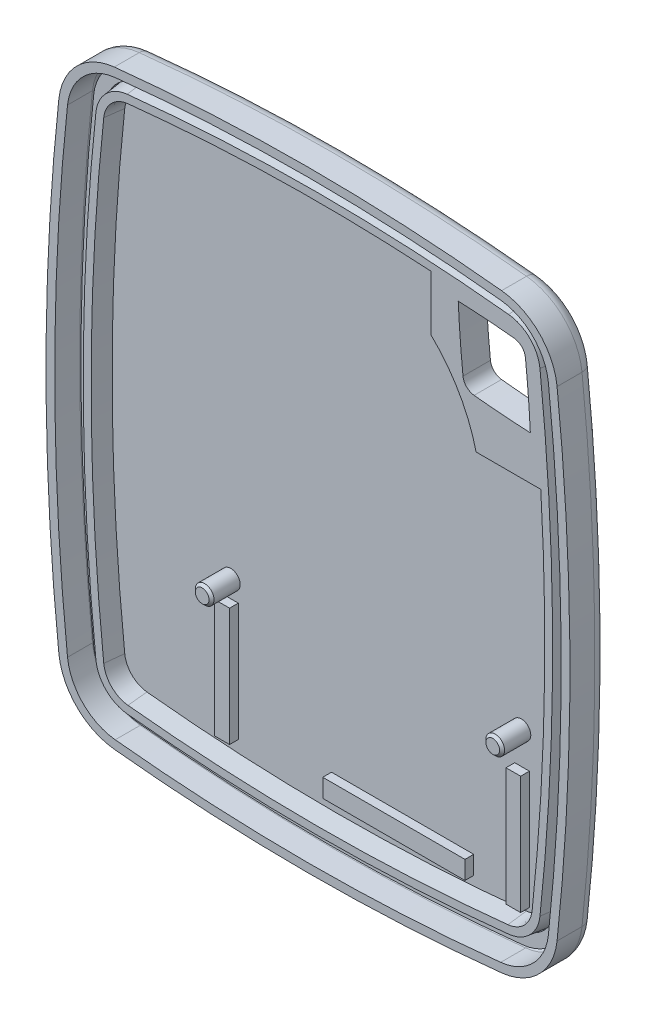
SolidWorks part; units mm, degrees
material "Özel Plastik"
ref_plane "Ön Düzlem" through (0, 0, 0) normal (0, 0, 1) x (1, 0, 0)
ref_plane "Üst Düzlem" through (0, 0, 0) normal (0, 1, 0) x (1, 0, 0)
ref_plane "Sağ Düzlem" through (0, 0, 0) normal (1, 0, 0) x (0, 0, -1)
sketch "Çizim1" plane through (0, 0, 0) normal (0, 0, 1) x (1, 0, 0)
  line L1 (-21, -24.5) -> (21, -24.5)
  line L2 (-21, -24.5) -> (-21, 24.5)
  line L3 (-21, 24.5) -> (21, 24.5)
  line L4 (21, -24.5) -> (21, 24.5)
  line L5 (-21, -24.5) -> (21, 24.5) construction
  line L6 (-21, 24.5) -> (21, -24.5) construction
  point P0 (0, 0)
  dimension "D1" = 42
  dimension "D2" = 49
extrude "Yükseklik-Ekstrüzyon1" add sketch "Çizim1" along normal mid plane 3 contours L3 L4 L1 L2
sketch "Çizim2" plane through (0, 0, 1.5) normal (0, 0, 1) x (1, 0, 0)
  line L0 (-21, 23) -> (21, 23) construction
  line L1 (-21, -24.5) -> (-21, 24.5) construction
  line L2 (21, -24.5) -> (21, 24.5) construction
  line L3 (-21, 24.5) -> (21, 24.5) construction
  line L4 (0, 0) -> (12.6557, 0) construction
  line L5 (-21, 24.5) -> (21, 24.5)
  line L6 (21, 24.5) -> (21, 23)
  line L7 (-21, 24.5) -> (-21, 23)
  line L8 (-21, -23) -> (21, -23) construction
  line L9 (-21, -24.5) -> (-21, -23)
  line L10 (21, -24.5) -> (21, -23)
  line L11 (-21, -24.5) -> (21, -24.5)
  arc A0 (-21, 23) -> (21, 23) centre (0, -123.25) cw
  arc A1 (-21, -23) -> (21, -23) centre (0, 123.25) ccw
  line M4 (-21, 24.5) -> (-21, -24.5)
  line M5 (-21, -24.5) -> (21, -24.5)
  line M6 (21, -24.5) -> (21, 24.5)
  line M7 (21, 24.5) -> (-21, 24.5)
  dimension "D1" = 1.5
extrude "Kes-Ekstrüzyon1" cut sketch "Çizim2" against normal through all contours A0 M7 M6 | A0 L5 M4 | A1 M4 M5 | A1 L11 M6 region at (-15.7553, 24.0504, 1.5) region at (15.7553, 24.0504, 1.5) region at (-15.7553, -24.0504, 1.5) region at (15.7553, -24.0504, 1.5)
sketch "Çizim3" plane through (0, 0, 1.5) normal (0, 0, 1) x (1, 0, 0)
  line L0 (19.5, 23.2075) -> (19.5, -23.2075) construction
  line L1 (21, -23) -> (21, 23) construction
  line L2 (21, 23) -> (21, -23)
  line L3 (0, 0) -> (0, -12.7146) construction
  line L4 (-19.5, 23.2075) -> (-19.5, -23.2075) construction
  line L5 (-21, 23) -> (-21, -23)
  arc A0 (21, 23) -> (-21, 23) centre (0, -123.25) ccw construction
  arc A1 (-21, -23) -> (21, -23) centre (0, 123.25) ccw construction
  arc A2 (19.5, 23.2075) -> (19.5, -23.2075) centre (-159.28, 0) cw
  arc A3 (19.5, -23.2075) -> (21, -23) centre (0, 123.25) ccw
  arc A4 (21, 23) -> (19.5, 23.2075) centre (0, -123.25) ccw
  arc A5 (-21, 23) -> (-19.5, 23.2075) centre (0, -123.25) cw
  arc A6 (-19.5, -23.2075) -> (-21, -23) centre (0, 123.25) cw
  arc A7 (-19.5, 23.2075) -> (-19.5, -23.2075) centre (159.28, 0) ccw
  arc M3 (-21, -23) -> (21, -23) centre (0, 123.25) ccw
  line M4 (21, -23) -> (21, 23)
  arc M5 (21, 23) -> (-21, 23) centre (0, -123.25) ccw
  line M6 (-21, 23) -> (-21, -23)
  dimension "D1" = 1.5
extrude "Kes-Ekstrüzyon2" cut sketch "Çizim3" against normal through all contours A2 L2 M5 | A2 M4 M3 | A7 L5 M3 | A7 M5 M6 region at (20.551, 17.3335, 1.5) region at (20.551, -17.3335, 1.5) region at (-20.551, 17.3335, 1.5) region at (-20.551, -17.3335, 1.5)
fillet "Radyus1" radius 5 4 edges at (-19.5, -23.2075, 0) (19.5, -23.2075, 0) (-19.5, 23.2075, 0) (19.5, 23.2075, 0)
fillet "Radyus2" radius 1 8 edges at (18.5311, 22.2484, -1.5) (0, 24.5, -1.5) (-18.5311, 22.2484, -1.5) (-21, 0, -1.5) (-18.5311, -22.2484, -1.5) (0, -24.5, -1.5) (18.5311, -22.2484, -1.5) (21, 0, -1.5)
shell "İç Boşaltma1" thickness 0.7 removed face at (0, 0, 1.5)
sketch "Çizim4" plane through (0, 0, -0.8) normal (0, 0, 1) x (1, 0, 0)
  arc A0 (15.3138, 21.6933) -> (-15.3138, 21.6933) centre (0, -123.25) ccw
  arc A1 (-15.3138, 21.6933) -> (-17.9814, 19.0301) centre (-14.9986, 18.7099) ccw
  arc A2 (-17.9814, 19.0301) -> (-17.9814, -19.0301) centre (159.28, 0) ccw
  arc A3 (-17.9814, -19.0301) -> (-15.3138, -21.6933) centre (-14.9986, -18.7099) ccw
  arc A4 (-15.3138, -21.6933) -> (15.3138, -21.6933) centre (0, 123.25) ccw
  arc A5 (15.3138, -21.6933) -> (17.9814, -19.0301) centre (14.9986, -18.7099) ccw
  arc A6 (17.9814, -19.0301) -> (17.9814, 19.0301) centre (-159.28, 0) ccw
  arc A7 (17.9814, 19.0301) -> (15.3138, 21.6933) centre (14.9986, 18.7099) ccw
  arc A8 (15.4188, 22.6877) -> (-15.4188, 22.6877) centre (0, -123.25) ccw
  arc A9 (-15.4188, 22.6877) -> (-18.9757, 19.1368) centre (-14.9986, 18.7099) ccw
  arc A10 (-18.9757, 19.1368) -> (-18.9757, -19.1368) centre (159.28, 0) ccw
  arc A11 (-18.9757, -19.1368) -> (-15.4188, -22.6877) centre (-14.9986, -18.7099) ccw
  arc A12 (-15.4188, -22.6877) -> (15.4188, -22.6877) centre (0, 123.25) ccw
  arc A13 (15.4188, -22.6877) -> (18.9757, -19.1368) centre (14.9986, -18.7099) ccw
  arc A14 (18.9757, -19.1368) -> (18.9757, 19.1368) centre (-159.28, 0) ccw
  arc A15 (18.9757, 19.1368) -> (15.4188, 22.6877) centre (14.9986, 18.7099) ccw
  arc A16 (15.4188, 22.6877) -> (-15.4188, 22.6877) centre (0, -123.25) ccw construction
  arc A17 (-15.4188, 22.6877) -> (-18.9757, 19.1368) centre (-14.9986, 18.7099) ccw construction
  arc A18 (-18.9757, 19.1368) -> (-18.9757, -19.1368) centre (159.28, 0) ccw construction
  arc A19 (-18.9757, -19.1368) -> (-15.4188, -22.6877) centre (-14.9986, -18.7099) ccw construction
  arc A20 (-15.4188, -22.6877) -> (15.4188, -22.6877) centre (0, 123.25) ccw construction
  arc A21 (15.4188, -22.6877) -> (18.9757, -19.1368) centre (14.9986, -18.7099) ccw construction
  arc A22 (18.9757, -19.1368) -> (18.9757, 19.1368) centre (-159.28, 0) ccw construction
  arc A23 (18.9757, 19.1368) -> (15.4188, 22.6877) centre (14.9986, 18.7099) ccw construction
  arc A24 (15.2087, 20.6988) -> (-15.2087, 20.6988) centre (0, -123.25) ccw
  arc A25 (-15.2087, 20.6988) -> (-16.9871, 18.9234) centre (-14.9986, 18.7099) ccw
  arc A26 (-16.9871, 18.9234) -> (-16.9871, -18.9234) centre (159.28, 0) ccw
  arc A27 (-16.9871, -18.9234) -> (-15.2087, -20.6988) centre (-14.9986, -18.7099) ccw
  arc A28 (-15.2087, -20.6988) -> (15.2087, -20.6988) centre (0, 123.25) ccw
  arc A29 (15.2087, -20.6988) -> (16.9871, -18.9234) centre (14.9986, -18.7099) ccw
  arc A30 (16.9871, -18.9234) -> (16.9871, 18.9234) centre (-159.28, 0) ccw
  arc A31 (16.9871, 18.9234) -> (15.2087, 20.6988) centre (14.9986, 18.7099) ccw
  dimension "D1" = 0
  dimension "D2" = 1
  dimension "D3" = 1
extrude "Yükseklik-Ekstrüzyon2" add sketch "Çizim4" along normal blind 1.5 draft 7
sketch "Çizim5" plane through (0, 0, -0.8) normal (0, 0, 1) x (1, 0, 0)
  arc A16 (15.3138, -21.6933) -> (17.9814, -19.0301) centre (14.9986, -18.7099) ccw construction
  arc A17 (17.9814, -19.0301) -> (17.9814, 19.0301) centre (-159.28, 0) ccw construction
  arc A18 (17.9814, 19.0301) -> (15.3138, 21.6933) centre (14.9986, 18.7099) ccw construction
  arc A19 (15.3138, 21.6933) -> (-15.3138, 21.6933) centre (0, -123.25) ccw construction
  arc A20 (-15.3138, 21.6933) -> (-17.9814, 19.0301) centre (-14.9986, 18.7099) ccw construction
  arc A21 (-17.9814, 19.0301) -> (-17.9814, -19.0301) centre (159.28, 0) ccw construction
  arc A22 (-17.9814, -19.0301) -> (-15.3138, -21.6933) centre (-14.9986, -18.7099) ccw construction
  arc A23 (-15.3138, -21.6933) -> (15.3138, -21.6933) centre (0, 123.25) ccw construction
  arc A24 (15.4188, 22.6877) -> (-15.4188, 22.6877) centre (0, -123.25) ccw
  arc A25 (-15.4188, 22.6877) -> (-18.9757, 19.1368) centre (-14.9986, 18.7099) ccw
  arc A26 (-18.9757, 19.1368) -> (-18.9757, -19.1368) centre (159.28, 0) ccw
  arc A27 (-18.9757, -19.1368) -> (-15.4188, -22.6877) centre (-14.9986, -18.7099) ccw
  arc A28 (-15.4188, -22.6877) -> (15.4188, -22.6877) centre (0, 123.25) ccw
  arc A29 (15.4188, -22.6877) -> (18.9757, -19.1368) centre (14.9986, -18.7099) ccw
  arc A30 (18.9757, -19.1368) -> (18.9757, 19.1368) centre (-159.28, 0) ccw
  arc A31 (18.9757, 19.1368) -> (15.4188, 22.6877) centre (14.9986, 18.7099) ccw
  arc A32 (15.4188, 22.6877) -> (-15.4188, 22.6877) centre (0, -123.25) ccw
  arc A33 (-15.4188, 22.6877) -> (-18.9757, 19.1368) centre (-14.9986, 18.7099) ccw
  arc A34 (-18.9757, 19.1368) -> (-18.9757, -19.1368) centre (159.28, 0) ccw
  arc A35 (-18.9757, -19.1368) -> (-15.4188, -22.6877) centre (-14.9986, -18.7099) ccw
  arc A36 (-15.4188, -22.6877) -> (15.4188, -22.6877) centre (0, 123.25) ccw
  arc A37 (15.4188, -22.6877) -> (18.9757, -19.1368) centre (14.9986, -18.7099) ccw
  arc A38 (18.9757, -19.1368) -> (18.9757, 19.1368) centre (-159.28, 0) ccw
  arc A39 (18.9757, 19.1368) -> (15.4188, 22.6877) centre (14.9986, 18.7099) ccw
  arc A40 (15.3138, -21.6933) -> (17.9814, -19.0301) centre (14.9986, -18.7099) ccw
  arc A41 (17.9814, -19.0301) -> (17.9814, 19.0301) centre (-159.28, 0) ccw
  arc A42 (17.9814, 19.0301) -> (15.3138, 21.6933) centre (14.9986, 18.7099) ccw
  arc A43 (15.3138, 21.6933) -> (-15.3138, 21.6933) centre (0, -123.25) ccw
  arc A44 (-15.3138, 21.6933) -> (-17.9814, 19.0301) centre (-14.9986, 18.7099) ccw
  arc A45 (-17.9814, 19.0301) -> (-17.9814, -19.0301) centre (159.28, 0) ccw
  arc A46 (-17.9814, -19.0301) -> (-15.3138, -21.6933) centre (-14.9986, -18.7099) ccw
  arc A47 (-15.3138, -21.6933) -> (15.3138, -21.6933) centre (0, 123.25) ccw
  dimension "D1" = 0
extrude "Yükseklik-Ekstrüzyon3" add sketch "Çizim5" along normal blind 0.5
sketch "Çizim8" plane through (0, 0, -0.8) normal (0, 0, 1) x (1, 0, 0)
  circle A0 centre (14.8124, -8.31) radius 0.75
  circle A1 centre (-8.4809, -9.5063) radius 0.75
  dimension "D1" = 1.5
  dimension "D4" = 1.5
extrude "Yükseklik-Ekstrüzyon8" add sketch "Çizim8" along normal up to surface (2.3 mm away) and the other way blind 0.2 up to face at (0, 0, 1.5)
sketch "Çizim16" plane through (0, 0, -0.8) normal (0, 0, 1) x (1, 0, 0)
  line L0 (9.0489, 21.4014) -> (9.0489, 16.9928)
  line L1 (9.7043, 21.6409) -> (15.8772, 21.1339)
  line L2 (12.6801, 10.6575) -> (18.1864, 10.6575)
  line L8 (15.8772, 21.1339) -> (17.3743, 19.6368)
  line L9 (17.3743, 19.6368) -> (18.0639, 12.7952)
  line L10 (18.0639, 12.7952) -> (18.1864, 10.6575)
  line L13 (9.0489, 21.4014) -> (9.7043, 21.6409)
  arc A0 (15.2281, 20.882) -> (-15.2281, 20.882) centre (0, -123.25) ccw construction
  arc A1 (12.6801, 10.6575) -> (9.0489, 16.9928) centre (0.0231, 7.6112) ccw
extrude "Yükseklik-Ekstrüzyon15" add sketch "Çizim16" along normal up to surface (1.5 mm away) up to face at (0, 0, 0.7)
sketch "Çizim6" plane through (0, 0, -0.8) normal (0, 0, 1) x (1, 0, 0)
  arc A3 (17.0273, 14.1641) -> (16.6317, 19.1951) centre (-71.5019, 9.7334) ccw
  arc A4 (16.6317, 19.1951) -> (15.7425, 20.0828) centre (15.6374, 19.0883) ccw
  arc A5 (15.7425, 20.0828) -> (11.2456, 20.4167) centre (8.1381, -51.8916) ccw
  arc A6 (11.2456, 20.4167) -> (11.629, 15.3988) centre (99.7842, 24.6571) ccw
  arc A7 (11.629, 15.3988) -> (12.5162, 14.509) centre (12.6235, 15.5032) ccw
  arc A8 (12.5162, 14.509) -> (17.0273, 14.1641) centre (20.2865, 86.4657) ccw
extrude "Kes-Ekstrüzyon3" cut sketch "Çizim6" against normal through all and the other way blind 10.4
chamfer "Pah3" distance 0.2 angle 45 2 edges at (14.0624, -8.31, 1.5) (-9.2309, -9.5063, 1.5)
sketch "Çizim22" plane through (0, 0, 0) normal (0, 0, 1) x (1, 0, 0)
  line B0 (8.748, -9.0009) -> (8.748, -15.6811)
  line B1 (-8.8452, -13.2677) -> (-8.8452, -14.7677)
  line B2 (-6.8452, -13.2677) -> (-6.8452, -14.7677)
  line B3 (-8.8452, -13.2677) -> (-6.8452, -13.2677)
  line B4 (-12.4952, -5.7677) -> (-3.4952, -5.7677)
  line B5 (-8.8452, -7.3177) -> (-6.8452, -7.3177)
  line B6 (-8.8452, -5.8177) -> (-8.8452, -7.3177)
  line B7 (-6.8452, -5.8177) -> (-6.8452, -7.3177)
  line B8 (-12.4952, -14.7677) -> (-3.4952, -14.7677)
  line B9 (-3.4952, -5.7677) -> (-3.4952, -7.9677)
  line B10 (-3.4952, -12.1177) -> (-3.4952, -14.7677)
  line B11 (-12.4952, -12.0677) -> (-12.4952, -14.7177)
  line B12 (-12.4952, -5.7677) -> (-12.4952, -7.9677)
  line B13 (3.1731, -14.1667) -> (3.6231, -14.1667)
  line B14 (4.0731, -14.1667) -> (3.8231, -14.4167)
  line B15 (4.0731, -14.1667) -> (4.2231, -14.1667)
  line B16 (4.2231, -14.1667) -> (4.6731, -14.1667)
  line B17 (4.6731, -13.4667) -> (4.6731, -14.7667)
  line B18 (3.1231, -13.4667) -> (4.6731, -13.4667)
  line B19 (3.1231, -13.4667) -> (3.1231, -14.7667)
  line B20 (3.1231, -14.7667) -> (4.6731, -14.7667)
  line B21 (2.198, -6.2343) -> (1.8445, -6.5878)
  line B22 (2.198, -6.2343) -> (2.5515, -6.5878)
  line B23 (-0.2769, -8.7091) -> (-0.6304, -9.0626)
  line B24 (-0.6304, -9.0626) -> (-0.2769, -9.4161)
  line B25 (1.8445, -11.5376) -> (2.198, -11.8911)
  line B26 (2.5515, -11.5376) -> (2.198, -11.8911)
  line B27 (5.0264, -9.0626) -> (4.6729, -9.4162)
  line B28 (4.6729, -8.7092) -> (5.0264, -9.0626)
  line B29 (-2.6927, -7.0792) -> (-2.6927, -10.2316)
  line B30 (-1.2926, -7.0792) -> (-1.2926, -10.2316)
  line B31 (-2.6927, -10.2316) -> (-1.2926, -10.2316)
  line B32 (-2.6927, -7.0792) -> (-1.2926, -7.0792)
  line B33 (-12.8877, -4.6129) -> (-12.8877, -7.7653)
  line B34 (-14.2878, -4.6129) -> (-14.2878, -7.7653)
  line B35 (-14.2878, -4.6129) -> (-12.8877, -4.6129)
  line B36 (-14.2878, -7.7653) -> (-12.8877, -7.7653)
  line B37 (0.0718, -10.8704) -> (0.4218, -10.8704)
  line B38 (0.4218, -10.8704) -> (0.4218, -11.2704)
  line B39 (0.4218, -12.7704) -> (0.4218, -13.1704)
  line B40 (0.0718, -13.1704) -> (0.4218, -13.1704)
  line B41 (-1.8281, -13.1704) -> (-1.4282, -13.1704)
  line B42 (-1.8281, -12.7704) -> (-1.8281, -13.1704)
  line B43 (-1.8281, -10.8704) -> (-1.8281, -11.2704)
  line B44 (-1.8281, -10.8704) -> (-1.4282, -10.8704)
  line B45 (-1.6781, -13.0204) -> (0.2719, -13.0204)
  line B46 (-1.6781, -11.0204) -> (-1.6781, -13.0204)
  line B47 (-1.6781, -11.0204) -> (0.2719, -11.0204)
  line B48 (0.2719, -11.0204) -> (0.2719, -13.0204)
  line B49 (-0.6781, -11.5204) -> (-0.6781, -12.5204)
  line B50 (-1.1782, -12.0204) -> (-0.1782, -12.0204)
  line B51 (8.2178, -3.2714) -> (8.2178, -12.6694)
  line B52 (6.2846, -2.9735) -> (6.8364, -3.5253)
  line B53 (3.8403, -3.7081) -> (3.8403, -4.1176)
  line B54 (3.8403, -3.1833) -> (3.8403, -3.7081)
  line B55 (6.8364, -3.5253) -> (6.8364, -4.5762)
  line B56 (4.0502, -2.9735) -> (3.8403, -3.1833)
  line B57 (4.0502, -2.9735) -> (6.2846, -2.9735)
  line B58 (-13.4328, -5.6125) -> (-10.5404, -5.6125)
  line B59 (-10.5304, -5.6025) -> (-10.5404, -5.6125)
  line B60 (-10.5304, -4.98) -> (-10.5304, -5.6025)
  line B61 (-10.5404, -5.6125) -> (-9.1554, -5.6125)
  line B62 (-9.1554, -5.6125) -> (-7.2124, -7.5555)
  line B63 (7.1437, -5.5515) -> (6.2268, -6.4685)
  line B64 (7.1437, -5.5515) -> (7.6619, -5.5515)
  line B65 (7.4917, -5.3879) -> (7.4917, -5.3923)
  line B66 (7.4689, -5.365) -> (7.4917, -5.3879)
  line B67 (3.8403, -4.1176) -> (4.0551, -4.3323)
  line B68 (4.1182, -6.324) -> (4.1182, -6.5767)
  line B69 (5.0017, -5.4406) -> (4.1182, -6.324)
  line B70 (5.0017, -5.4406) -> (5.6166, -5.4406)
  line B71 (7.507, -12.2522) -> (7.3901, -12.369)
  line B72 (7.507, -11.3757) -> (7.507, -12.2522)
  line B73 (5.6578, -12.7245) -> (5.9719, -13.0385)
  line B74 (5.6578, -11.518) -> (5.6578, -12.7245)
  line B75 (5.3073, -11.1675) -> (5.6578, -11.518)
  line B76 (3.8597, -10.1587) -> (4.2106, -10.5096)
  line B77 (4.2106, -10.5096) -> (6.6764, -10.5096)
  line B78 (6.6764, -10.5096) -> (7.507, -11.3402)
  line B79 (7.507, -11.3402) -> (7.507, -11.3757)
  line B80 (6.3284, -13.0469) -> (6.3284, -13.9081)
  line B81 (3.5769, -10.4415) -> (4.3028, -11.1675)
  line B82 (4.3028, -11.1675) -> (5.3073, -11.1675)
  line B83 (5.9719, -13.0385) -> (6.3368, -13.0385)
  line B84 (2.7283, -11.29) -> (3.4557, -12.0174)
  line B85 (4.1135, -12.1733) -> (4.1564, -12.1733)
  line B86 (4.1669, -12.1629) -> (4.1564, -12.1733)
  line B87 (3.0112, -11.0072) -> (4.1669, -12.1629)
  line B88 (3.3693, -12.0768) -> (3.3962, -12.0768)
  line B89 (3.4557, -12.0174) -> (3.3962, -12.0768)
  line B90 (0.8191, -7.6838) -> (2.198, -9.0626)
  line B91 (1.6323, -9.0626) -> (2.198, -9.0626)
  line B92 (0.5363, -7.9666) -> (1.6323, -9.0626)
  line B93 (2.7683, -9.671) -> (2.198, -10.2056)
  line B94 (2.6726, -9.3158) -> (2.198, -10.2056)
  line B95 (3.0108, -9.4436) -> (2.7683, -9.671)
  line B96 (2.6944, -9.2749) -> (2.6726, -9.3158)
  line B97 (3.0108, -8.6816) -> (2.6944, -9.2749)
  line B98 (3.3805, -9.1138) -> (4.1425, -9.8758)
  line B99 (5.7695, -5.1737) -> (5.7695, -5.2702)
  line B100 (5.7695, -4.9298) -> (5.7695, -5.1737)
  line B101 (5.9829, -4.6432) -> (5.9829, -4.7164)
  line B102 (5.9829, -4.7164) -> (5.9357, -4.7636)
  line B103 (4.1182, -6.5767) -> (3.294, -7.4009)
  line B104 (5.9118, -5.1455) -> (5.6166, -5.4406)
  line B105 (5.9118, -4.8566) -> (5.9118, -5.1455)
  line B106 (5.9118, -4.7956) -> (5.9118, -4.8566)
  line B107 (5.9357, -4.7636) -> (5.8061, -4.8932)
  line B108 (5.8061, -4.8932) -> (5.7695, -4.9298)
  line B109 (3.2696, -4.8566) -> (3.5113, -5.0984)
  line B110 (3.5113, -5.0984) -> (3.5113, -6.6179)
  line B111 (3.5113, -6.6179) -> (3.0112, -7.1181)
  line B112 (2.5731, -13.7667) -> (2.5731, -14.5167)
  line B113 (1.1052, -6.2728) -> (1.6677, -6.8353)
  line B114 (1.67, -11.2924) -> (2.0307, -11.2924)
  line B115 (2.4483, -6.8353) -> (2.7283, -6.8353)
  line B116 (4.7922, -6.4685) -> (6.2268, -6.4685)
  line B117 (4.7922, -6.4685) -> (3.5769, -7.6838)
  line B118 (-7.2124, -7.5555) -> (-5.0818, -7.5555)
  line B119 (-13.8697, -5.1756) -> (-13.4328, -5.6125)
  line B120 (-13.8697, -6.7504) -> (-12.2492, -6.7504)
  line B121 (-12.2492, -6.7504) -> (-10.4432, -8.5563)
  line B122 (-10.4432, -8.5563) -> (-5.7391, -8.5563)
  line B123 (-5.6121, -8.4293) -> (-5.7391, -8.5563)
  line B124 (2.0307, -11.2924) -> (2.6987, -11.9604)
  line B125 (4.7127, -7.1136) -> (5, -7.1136)
  line B126 (4.7127, -7.1136) -> (3.8597, -7.9666)
  line B127 (0.8413, -7.1403) -> (1.102, -7.4009)
  line B128 (1.6037, -5.9907) -> (1.6338, -5.9907)
  line B129 (1.6037, -5.9907) -> (2.4483, -6.8353)
  line B130 (-2.3178, -6.8316) -> (-2.3178, -7.7258)
  line B131 (0.5601, -6.0417) -> (0.8741, -6.0417)
  line B132 (0.8741, -6.0417) -> (1.1052, -6.2728)
  line B133 (-2.3178, -6.8291) -> (-2.3178, -6.8316)
  line B134 (-2.9604, -6.1865) -> (-2.3178, -6.8291)
  line B135 (-2.9604, -6.1865) -> (-2.8004, -6.1865)
  line B136 (3.294, -10.7243) -> (4.6139, -12.0442)
  line B137 (4.6139, -12.0442) -> (4.6139, -12.1174)
  line B138 (-0.0569, -7.9391) -> (0.2534, -8.2495)
  line B139 (-0.6185, -7.9391) -> (-0.0569, -7.9391)
  line B140 (1.8148, -14.853) -> (2.2369, -14.853)
  line B141 (2.5731, -14.5167) -> (2.2369, -14.853)
  line B142 (0.6219, -11.6204) -> (1.0765, -11.6204)
  line B143 (-0.2593, -11.0201) -> (0.3907, -11.6701)
  line B144 (-0.6781, -10.7204) -> (-0.2781, -10.7204)
  line B145 (1.0765, -11.6204) -> (1.6584, -12.2024)
  line B146 (1.6584, -12.2024) -> (1.9229, -12.2024)
  line B147 (0.6219, -12.0204) -> (1.0241, -12.0204)
  line B148 (4.685, -12.0565) -> (4.8247, -12.0565)
  line B149 (4.6749, -12.0565) -> (4.6139, -12.1174)
  line B150 (4.6749, -12.0565) -> (4.8247, -12.0565)
  line B151 (1.1674, -14.5242) -> (1.1674, -14.9732)
  line B152 (-2.4583, -11.6204) -> (-2.8969, -12.059)
  line B153 (-2.4583, -11.6204) -> (-1.9781, -11.6204)
  line B154 (0.4458, -12.5965) -> (0.4458, -13.2528)
  line B155 (0.6219, -12.4204) -> (0.4458, -12.5965)
  line B156 (-1.9781, -12.0204) -> (-0.6781, -12.0204)
  line B157 (-3.4952, -14.7677) -> (-3.4775, -14.7677)
  line B158 (-12.2952, -10.0177) -> (-12.2952, -12.3203)
  line B159 (-12.2952, -12.3203) -> (-11.7437, -12.8718)
  line B160 (1.1674, -14.9732) -> (0.8178, -15.3229)
  line B161 (-0.6781, -13.3204) -> (-0.6781, -14.0744)
  line B162 (-0.6781, -14.0744) -> (-0.8369, -14.2332)
  line B163 (-0.8369, -14.2332) -> (-0.8369, -15.074)
  line B164 (-0.8369, -15.074) -> (-0.588, -15.3229)
  line B165 (-0.588, -15.3229) -> (0.8178, -15.3229)
  line B166 (-0.2781, -13.3204) -> (-0.2807, -13.323)
  line B167 (-0.2807, -13.323) -> (-0.2807, -14.8301)
  line B168 (-0.174, -14.66) -> (-0.2807, -14.7666)
  line B169 (-0.2807, -14.7666) -> (-0.2807, -14.8301)
  line B170 (-3.4775, -14.7677) -> (-2.9045, -15.3407)
  line B171 (-0.6185, -7.9391) -> (-0.9665, -8.2871)
  line B172 (-0.9665, -8.2871) -> (-0.9665, -9.2785)
  line B173 (-1.9723, -9.8797) -> (-2.013, -9.9203)
  line B174 (1.0171, -6.7504) -> (1.3848, -7.1181)
  line B175 (-2.2365, -6.7504) -> (-2.3178, -6.8316)
  line B176 (-2.2365, -6.7504) -> (1.0171, -6.7504)
  line B177 (-1.0794, -7.1504) -> (-1.1671, -7.2381)
  line B178 (-1.0794, -7.1504) -> (0.8313, -7.1504)
  line B179 (-1.0782, -10.1996) -> (-1.0782, -10.7204)
  line B180 (-0.2375, -9.359) -> (-1.0782, -10.1996)
  line B181 (-0.2375, -8.7404) -> (-0.2375, -9.359)
  line B182 (-0.0294, -8.5323) -> (-0.2375, -8.7404)
  line B183 (-0.6781, -10.7204) -> (-0.6781, -11.1052)
  line B184 (-0.6781, -11.1052) -> (-0.8496, -11.2767)
  line B185 (-1.9781, -12.4204) -> (-2.5489, -12.9912)
  line B186 (-3.5952, -10.0177) -> (-3.5952, -12.6814)
  line B187 (-3.5952, -12.6814) -> (-3.2855, -12.9912)
  line B188 (-3.2855, -12.9912) -> (-2.5489, -12.9912)
  line B189 (-2.013, -9.9203) -> (-2.018, -9.9254)
  line B190 (-2.018, -9.9254) -> (-2.018, -10.3775)
  line B191 (-2.018, -10.3775) -> (-1.6781, -10.7174)
  line B192 (-1.6781, -10.7174) -> (-1.6781, -11.0204)
  line B193 (-1.6781, -11.0204) -> (-1.4219, -11.2767)
  line B194 (-1.4219, -11.2767) -> (-0.8496, -11.2767)
  line B195 (1.0241, -12.0204) -> (1.3246, -12.321)
  line B196 (1.3246, -12.321) -> (1.3246, -13.0971)
  line B197 (1.3246, -13.0971) -> (1.1674, -13.2542)
  line B198 (-2.9045, -15.3407) -> (-1.3449, -15.3407)
  line B199 (-1.0782, -13.3204) -> (-1.0782, -15.0739)
  line B200 (-1.0782, -15.0739) -> (-1.3449, -15.3407)
  line B201 (-2.8791, -13.6262) -> (-2.8791, -14.4491)
  line B202 (-2.8791, -14.4491) -> (-2.5565, -14.7717)
  line B203 (7.166, -1.6806) -> (6.5335, -2.3131)
  line B204 (6.5335, -2.3131) -> (6.5335, -3.2351)
  line B205 (4.0449, -3.6059) -> (2.351, -5.2999)
  line B206 (4.0449, -3.6059) -> (4.6291, -3.6059)
  line B207 (4.6291, -3.6059) -> (6.4156, -5.3923)
  line B208 (6.4156, -5.3923) -> (7.4917, -5.3923)
  line B209 (4.0551, -4.3323) -> (4.1615, -4.3323)
  line B210 (4.1615, -4.3323) -> (4.2456, -4.4164)
  line B211 (4.2456, -4.4164) -> (3.3148, -5.3472)
  line B212 (1.5303, -14.853) -> (1.8148, -14.853)
  line B213 (0.8141, -14.1367) -> (1.5303, -14.853)
  line B214 (0.8141, -12.1581) -> (0.8141, -14.1367)
  line B215 (-0.9665, -10.3775) -> (0.8141, -12.1581)
  line B216 (3.3693, -12.0768) -> (3.3693, -13.0491)
  line B217 (3.3693, -13.0491) -> (2.7353, -13.6831)
  line B218 (4.1135, -12.1733) -> (4.1135, -13.4509)
  line B219 (4.1135, -13.4509) -> (4.1669, -13.5042)
  line B220 (2.6581, -12.3308) -> (1.6192, -13.3696)
  line B221 (2.6581, -12.0438) -> (2.6581, -12.3308)
  line B222 (5.2362, -12.7397) -> (5.2362, -13.3671)
  line B223 (2.8562, -13.7336) -> (2.8562, -13.7684)
  line B224 (3.9967, -13.6744) -> (4.0053, -13.6831)
  line B225 (1.6192, -13.3696) -> (1.6192, -13.6846)
  line B226 (1.6192, -13.6846) -> (1.6243, -13.6897)
  line B227 (5, -7.0527) -> (5, -7.1136)
  line B228 (-5.2541, -6.8775) -> (-6.0897, -7.7131)
  line B229 (-6.0897, -7.7131) -> (-6.0897, -8.95)
  line B230 (-2.3447, -12.695) -> (-2.3447, -13.6831)
  line B231 (-6.0897, -8.95) -> (-2.3447, -12.695)
  line B232 (-5.2541, -6.8775) -> (-2.4042, -6.8775)
  line B233 (-1.466, -5.9393) -> (-2.4042, -6.8775)
  line B234 (1.6338, -5.9907) -> (1.2728, -6.3516)
  line B235 (-1.466, -5.9393) -> (0.8022, -5.9393)
  line B236 (1.4416, -5.2999) -> (0.8022, -5.9393)
  line B237 (1.4416, -5.2999) -> (2.351, -5.2999)
  line B238 (0.2553, -6.9637) -> (1.6983, -6.9637)
  line B239 (3.3148, -5.3472) -> (1.6983, -6.9637)
  line B240 (3.3148, -5.3472) -> (5, -7.0323)
  line B241 (5, -7.0323) -> (5, -7.0527)
  line B242 (-4.7358, -7.2127) -> (-5.0787, -7.5556)
  line B243 (-4.7358, -7.2127) -> (-2.0317, -7.2127)
  line B244 (-5.4775, -8.4776) -> (-5.0584, -8.4776)
  line B245 (-4.2151, -7.6343) -> (-1.4161, -7.6343)
  line B246 (-4.2151, -7.6343) -> (-5.0584, -8.4776)
  line B247 (4.6241, -12.1276) -> (5.2362, -12.7397)
  line B248 (4.6952, -12.0565) -> (4.6241, -12.1276)
  line B249 (4.6952, -12.0565) -> (4.8247, -12.0565)
  line B250 (4.1669, -13.5042) -> (3.9967, -13.6744)
  line B251 (-4.4539, -13.7913) -> (-3.4775, -14.7677)
  line B252 (-9.7066, -13.7913) -> (-4.4539, -13.7913)
  line B253 (-10.6261, -12.8718) -> (-9.7066, -13.7913)
  line B254 (-11.7437, -12.8718) -> (-10.6261, -12.8718)
  line B255 (-0.3366, -14.6142) -> (-0.2807, -14.6701)
  line B256 (-0.2807, -14.6701) -> (-0.2807, -14.8301)
  line B257 (-0.9665, -9.2785) -> (-0.9665, -10.3775)
  line B258 (-1.1706, -6.3516) -> (1.2728, -6.3516)
  line B259 (-1.1706, -6.3516) -> (-2.0317, -7.2127)
  line B260 (-1.1671, -7.3854) -> (-1.4161, -7.6343)
  line B261 (-1.1671, -7.2381) -> (-1.1671, -7.3854)
  line B262 (-2.018, -10.3775) -> (-2.018, -11.4697)
  line B263 (-2.018, -9.2371) -> (-2.018, -10.3775)
  line B264 (-2.018, -11.4697) -> (0.1953, -13.6831)
  line B265 (0.2553, -6.9637) -> (-2.018, -9.2371)
  line B266 (-0.3366, -14.6142) -> (-0.6896, -14.9673)
  line B267 (-2.5565, -14.7717) -> (-2.3609, -14.9673)
  line B268 (-2.3609, -14.9673) -> (-0.6896, -14.9673)
  line B269 (14.6132, 4.1679) -> (6.6046, 4.1665)
  line B270 (-14.6339, -2.1495) -> (-10.9388, -2.1495)
  line B271 (9.8514, -14.8124) -> (10.2512, -14.8124)
  line B272 (10.2512, -14.8124) -> (10.4512, -14.6124)
  line B273 (10.4512, -14.6124) -> (10.2512, -14.4125)
  line B274 (10.2512, -14.4125) -> (9.8514, -14.4125)
  line B275 (9.8514, -14.4125) -> (10.1513, -14.4125)
  line B276 (10.1513, -14.4125) -> (10.1513, -14.8124)
  line B277 (9.8514, -14.2126) -> (10.4512, -14.2126)
  line B278 (10.4512, -14.2126) -> (9.8514, -13.8127)
  line B279 (9.8514, -13.8127) -> (10.4512, -13.8127)
  line B280 (10.4512, -13.6128) -> (10.4512, -13.2129)
  line B281 (10.4512, -13.2129) -> (10.4512, -13.4128)
  line B282 (10.4512, -13.4128) -> (9.8514, -13.4128)
  line B283 (10.4512, -12.6131) -> (10.4512, -13.0129)
  line B284 (10.4512, -13.0129) -> (9.8514, -13.0129)
  line B285 (9.8514, -13.0129) -> (9.8514, -12.6131)
  line B286 (10.1513, -13.0129) -> (10.1513, -12.813)
  line B287 (9.8514, -12.4131) -> (10.4512, -12.4131)
  line B288 (10.4512, -12.4131) -> (9.8514, -12.0133)
  line B289 (9.8514, -12.0133) -> (10.4512, -12.0133)
  line B290 (10.4512, -11.2135) -> (10.3512, -11.2135)
  line B291 (10.3512, -11.2135) -> (10.1513, -11.0136)
  line B292 (10.1513, -11.0136) -> (10.3512, -10.8137)
  line B293 (10.3512, -10.8137) -> (10.4512, -10.8137)
  line B294 (10.1513, -11.0136) -> (9.8514, -11.0136)
  line B295 (10.2512, -10.6137) -> (10.2512, -10.5138)
  line B296 (10.2512, -10.5138) -> (10.1513, -10.5138)
  line B297 (10.1513, -10.5138) -> (10.1513, -10.6137)
  line B298 (10.1513, -10.6137) -> (10.2512, -10.6137)
  line B299 (9.9513, -10.6137) -> (9.9513, -10.5138)
  line B300 (9.9513, -10.5138) -> (9.8514, -10.5138)
  line B301 (9.8514, -10.5138) -> (9.8514, -10.6137)
  line B302 (9.8514, -10.6137) -> (9.9513, -10.6137)
  line B303 (9.8514, -9.5141) -> (10.4512, -9.5141)
  line B304 (10.4512, -9.5141) -> (10.4512, -9.2142)
  line B305 (10.4512, -9.2142) -> (10.3512, -9.1142)
  line B306 (10.3512, -9.1142) -> (10.1513, -9.1142)
  line B307 (10.1513, -9.1142) -> (10.0513, -9.2142)
  line B308 (10.0513, -9.2142) -> (10.0513, -9.5141)
  line B309 (10.3512, -8.5144) -> (10.4512, -8.6144)
  line B310 (10.4512, -8.6144) -> (10.4512, -8.8143)
  line B311 (10.4512, -8.8143) -> (10.3512, -8.9143)
  line B312 (10.3512, -8.9143) -> (9.9513, -8.9143)
  line B313 (9.9513, -8.9143) -> (9.8514, -8.8143)
  line B314 (9.8514, -8.8143) -> (9.8514, -8.6144)
  line B315 (9.8514, -8.6144) -> (9.9513, -8.5144)
  line B316 (10.4512, -8.3145) -> (9.8514, -8.3145)
  line B317 (9.8514, -8.3145) -> (9.8514, -8.0146)
  line B318 (9.8514, -8.0146) -> (9.9513, -7.9146)
  line B319 (9.9513, -7.9146) -> (10.0513, -7.9146)
  line B320 (10.0513, -7.9146) -> (10.1513, -8.0146)
  line B321 (10.1513, -8.0146) -> (10.1513, -8.3145)
  line B322 (10.1513, -8.3145) -> (10.1513, -8.0146)
  line B323 (10.1513, -8.0146) -> (10.2512, -7.9146)
  line B324 (10.2512, -7.9146) -> (10.3512, -7.9146)
  line B325 (10.3512, -7.9146) -> (10.4512, -8.0146)
  line B326 (10.4512, -8.0146) -> (10.4512, -8.3145)
  line B327 (12.7804, -14.3044) -> (12.7804, -13.9045)
  line B328 (12.7804, -13.9045) -> (12.7804, -14.1044)
  line B329 (12.7804, -14.1044) -> (12.1806, -14.1044)
  line B330 (12.1806, -13.7046) -> (12.7804, -13.7046)
  line B331 (12.7804, -13.7046) -> (12.7804, -13.4047)
  line B332 (12.7804, -13.4047) -> (12.6804, -13.3047)
  line B333 (12.6804, -13.3047) -> (12.4805, -13.3047)
  line B334 (12.4805, -13.3047) -> (12.3805, -13.4047)
  line B335 (12.3805, -13.4047) -> (12.3805, -13.7046)
  line B336 (12.3805, -13.5046) -> (12.1806, -13.3047)
  line B337 (12.7804, -13.1048) -> (12.7804, -12.9048)
  line B338 (12.7804, -12.9048) -> (12.7804, -13.0048)
  line B339 (12.7804, -13.0048) -> (12.1806, -13.0048)
  line B340 (12.1806, -13.0048) -> (12.1806, -13.1048)
  line B341 (12.1806, -13.1048) -> (12.1806, -12.9048)
  line B342 (12.7804, -12.305) -> (12.7804, -12.5049)
  line B343 (12.7804, -12.5049) -> (12.6804, -12.6049)
  line B344 (12.6804, -12.6049) -> (12.2805, -12.6049)
  line B345 (12.2805, -12.6049) -> (12.1806, -12.5049)
  line B346 (12.1806, -12.5049) -> (12.1806, -12.305)
  line B347 (12.1806, -12.305) -> (12.2805, -12.205)
  line B348 (12.2805, -12.205) -> (12.6804, -12.205)
  line B349 (12.6804, -12.205) -> (12.7804, -12.305)
  line B350 (12.0806, -12.0051) -> (12.0806, -11.6052)
  line B351 (12.7804, -11.0054) -> (12.7804, -11.4053)
  line B352 (12.7804, -11.4053) -> (12.4805, -11.4053)
  line B353 (12.4805, -11.4053) -> (12.4805, -11.2054)
  line B354 (12.4805, -11.2054) -> (12.4805, -11.4053)
  line B355 (12.4805, -11.4053) -> (12.1806, -11.4053)
  line B356 (12.7804, -10.8055) -> (12.7804, -10.6056)
  line B357 (12.7804, -10.6056) -> (12.7804, -10.7055)
  line B358 (12.7804, -10.7055) -> (12.1806, -10.7055)
  line B359 (12.1806, -10.7055) -> (12.1806, -10.8055)
  line B360 (12.1806, -10.8055) -> (12.1806, -10.6056)
  line B361 (12.1806, -10.3057) -> (12.7804, -10.3057)
  line B362 (12.7804, -10.3057) -> (12.1806, -9.9058)
  line B363 (12.1806, -9.9058) -> (12.7804, -9.9058)
  line B364 (12.7804, -9.7059) -> (12.1806, -9.7059)
  line B365 (12.1806, -9.7059) -> (12.1806, -9.406)
  line B366 (12.1806, -9.406) -> (12.2805, -9.306)
  line B367 (12.2805, -9.306) -> (12.6804, -9.306)
  line B368 (12.6804, -9.306) -> (12.7804, -9.406)
  line B369 (12.7804, -9.406) -> (12.7804, -9.7059)
  line B370 (12.1806, -9.1061) -> (12.7804, -9.1061)
  line B371 (12.7804, -9.1061) -> (12.5804, -8.9061)
  line B372 (12.5804, -8.9061) -> (12.7804, -8.7062)
  line B373 (12.7804, -8.7062) -> (12.1806, -8.7062)
  line B374 (12.7804, -8.1064) -> (12.7804, -8.5062)
  line B375 (12.7804, -8.5062) -> (12.1806, -8.5062)
  line B376 (12.1806, -8.5062) -> (12.1806, -8.1064)
  line B377 (12.4805, -8.5062) -> (12.4805, -8.3063)
  line B378 (11.4697, -12.6559) -> (11.0698, -12.6559)
  line B379 (11.0698, -12.6559) -> (10.8699, -12.456)
  line B380 (10.8699, -12.456) -> (11.0698, -12.256)
  line B381 (11.0698, -12.256) -> (11.4697, -12.256)
  line B382 (10.8699, -12.0561) -> (10.8699, -11.8562)
  line B383 (10.8699, -11.8562) -> (10.8699, -11.9561)
  line B384 (10.8699, -11.9561) -> (11.4697, -11.9561)
  line B385 (11.4697, -11.9561) -> (11.3697, -12.0561)
  line B386 (10.7699, -11.5563) -> (10.7699, -11.1564)
  line B387 (10.8699, -10.9565) -> (10.8699, -10.7565)
  line B388 (10.8699, -10.7565) -> (10.8699, -10.8565)
  line B389 (10.8699, -10.8565) -> (11.4697, -10.8565)
  line B390 (11.4697, -10.8565) -> (11.3697, -10.9565)
  line B391 (4.0276, -8.1848) -> (4.0473, -8.2045)
  line B392 (4.0473, -8.2045) -> (4.4271, -7.8247)
  line B393 (4.4271, -7.8247) -> (4.4074, -7.805)
  line B394 (4.4074, -7.805) -> (4.0276, -8.1848)
  line B395 (4.8269, -8.9483) -> (4.8269, -8.1355)
  line B396 (4.8269, -8.1355) -> (4.6821, -8.1355)
  line B397 (4.6821, -8.1355) -> (4.1779, -8.6398)
  line B398 (4.1779, -8.6398) -> (4.4864, -8.9483)
  line B399 (4.4864, -8.9483) -> (4.8269, -8.9483)
  line B400 (5.6499, -9.1846) -> (4.6759, -9.1769)
  line B401 (4.6759, -9.1769) -> (4.2681, -9.1744)
  line B402 (4.2681, -9.1744) -> (4.0954, -9.1744)
  line B403 (4.0954, -9.1744) -> (3.892, -9.0603)
  line B404 (3.892, -9.0603) -> (3.6826, -8.8509)
  line B405 (3.6826, -8.8509) -> (4.7255, -7.8081)
  line B406 (4.7255, -7.8081) -> (4.5842, -7.6668)
  line B407 (4.5842, -7.6668) -> (3.1885, -9.0625)
  line B408 (3.1885, -9.0625) -> (3.5391, -9.4132)
  line B409 (3.5391, -9.4132) -> (4.415, -10.2891)
  line B410 (4.415, -10.2891) -> (4.8247, -10.2891)
  line B411 (4.8247, -10.2891) -> (5.1419, -9.972)
  line B412 (5.1419, -9.972) -> (5.6499, -9.972)
  line B413 (5.6499, -9.972) -> (5.6499, -9.1846)
  line B414 (8.8214, -0.9084) -> (8.8214, -1.245)
  line B415 (8.8214, -1.245) -> (8.8214, -1.358)
  line B416 (8.8214, -1.358) -> (8.8214, -4.1444)
  line B417 (8.8214, -4.1444) -> (4.7028, -1.6145)
  line B418 (4.7028, -1.6145) -> (5.0238, -1.0063)
  line B419 (5.0238, -1.0063) -> (5.9549, 0.7579)
  line B420 (5.9549, 0.7579) -> (6.4693, 0.4392)
  line B421 (6.4693, 0.4392) -> (8.8214, -0.9084)
  line B422 (8.8214, -0.9084) -> (8.8214, -1.245)
  line B423 (8.8214, -1.245) -> (8.8214, -1.358)
  line B424 (8.8214, -1.358) -> (8.8214, -4.1444)
  line B425 (8.8214, -4.1444) -> (4.7028, -1.6145)
  line B426 (4.7028, -1.6145) -> (5.0238, -1.0063)
  line B427 (5.0238, -1.0063) -> (5.9549, 0.7579)
  line B428 (5.9549, 0.7579) -> (6.4693, 0.4392)
  line B429 (6.4693, 0.4392) -> (8.8214, -0.9084)
  line B430 (6.9118, -12.4549) -> (6.8118, -12.6135)
  line B431 (6.8118, -12.6135) -> (6.7532, -12.6135)
  line B432 (6.7532, -12.6135) -> (5.8618, -12.6135)
  line B433 (5.8618, -12.6135) -> (5.8348, -12.4247)
  line B434 (5.8348, -12.4247) -> (5.8348, -11.518)
  line B435 (5.8348, -11.518) -> (5.783, -11.3928)
  line B436 (5.783, -11.3928) -> (5.4324, -11.0423)
  line B437 (5.4324, -11.0423) -> (5.3073, -10.9905)
  line B438 (5.3073, -10.9905) -> (4.4296, -10.9905)
  line B439 (4.4296, -10.9905) -> (4.3456, -10.8826)
  line B440 (4.3456, -10.8826) -> (4.4335, -10.6866)
  line B441 (4.4335, -10.6866) -> (6.1128, -10.6866)
  line B442 (6.1128, -10.6866) -> (6.2694, -11.8889)
  line B443 (6.2694, -11.8889) -> (6.9118, -11.8889)
  line B444 (6.9118, -11.8889) -> (6.9118, -12.4549)
  line B445 (6.0472, -10.1824) -> (5.9152, -10.3326)
  line B446 (5.9152, -10.3326) -> (4.3377, -10.3326)
  line B447 (4.3377, -10.3326) -> (3.8393, -9.8342)
  line B448 (3.8393, -9.8342) -> (4.472, -9.2015)
  line B449 (4.472, -9.2015) -> (5.9195, -9.2015)
  line B450 (5.9195, -9.2015) -> (6.0472, -10.1824)
  line B451 (7.8924, -7.8678) -> (6.5189, -7.8678)
  line B452 (6.5189, -7.8678) -> (5.4877, -7.8678)
  line B453 (5.4877, -7.8678) -> (4.5305, -7.8678)
  line B454 (4.5305, -7.8678) -> (4.4568, -7.6899)
  line B455 (4.4568, -7.6899) -> (4.4803, -7.6352)
  line B456 (4.4803, -7.6352) -> (4.672, -7.4434)
  line B457 (4.672, -7.4434) -> (5, -7.5793)
  line B458 (5, -7.5793) -> (5.3292, -7.4429)
  line B459 (5.3292, -7.4429) -> (5.4656, -7.1136)
  line B460 (5.4656, -7.1136) -> (5.3709, -6.8849)
  line B461 (5.3709, -6.8849) -> (5.4911, -6.6849)
  line B462 (5.4911, -6.6849) -> (6.2268, -6.6849)
  line B463 (6.2268, -6.6849) -> (6.3799, -6.6215)
  line B464 (6.3799, -6.6215) -> (6.7377, -6.2637)
  line B465 (6.7377, -6.2637) -> (7.1904, -6.2637)
  line B466 (7.1904, -6.2637) -> (7.1904, -5.9451)
  line B467 (7.1904, -5.9451) -> (7.3904, -5.816)
  line B468 (7.3904, -5.816) -> (7.4917, -5.858)
  line B469 (7.4917, -5.858) -> (7.6924, -5.7748)
  line B470 (7.6924, -5.7748) -> (7.8924, -5.9085)
  line B471 (7.8924, -5.9085) -> (7.8924, -7.8678)
  line B472 (8.2429, -15.1522) -> (2.0909, -15.4208)
  line B473 (2.0909, -15.4208) -> (2.0469, -15.2225)
  line B474 (2.0469, -15.2225) -> (2.1441, -15.1823)
  line B475 (2.1441, -15.1823) -> (2.2072, -15.03)
  line B476 (2.2072, -15.03) -> (2.2369, -15.03)
  line B477 (2.2369, -15.03) -> (2.362, -14.9781)
  line B478 (2.362, -14.9781) -> (2.4984, -14.8417)
  line B479 (2.4984, -14.8417) -> (2.9731, -14.8417)
  line B480 (2.9731, -14.8417) -> (2.9731, -14.1917)
  line B481 (2.9731, -14.1917) -> (2.9731, -14.0917)
  line B482 (2.9731, -14.0917) -> (2.9731, -13.4417)
  line B483 (2.9731, -13.4417) -> (2.1731, -13.4417)
  line B484 (2.1731, -13.4417) -> (2.1731, -14.0917)
  line B485 (2.1731, -14.0917) -> (2.1731, -14.1917)
  line B486 (2.1731, -14.1917) -> (2.1172, -14.3357)
  line B487 (2.1172, -14.3357) -> (1.9229, -14.4321)
  line B488 (1.9229, -14.4321) -> (1.8148, -14.3874)
  line B489 (1.8148, -14.3874) -> (1.6877, -14.44)
  line B490 (1.6877, -14.44) -> (1.5214, -14.3289)
  line B491 (1.5214, -14.3289) -> (1.5214, -14.1067)
  line B492 (1.5214, -14.1067) -> (0.8134, -14.1067)
  line B493 (0.8134, -14.1067) -> (0.8134, -14.9417)
  line B494 (0.8134, -14.9417) -> (0.8298, -14.9813)
  line B495 (0.8298, -14.9813) -> (0.7003, -15.1459)
  line B496 (0.7003, -15.1459) -> (0.2341, -15.1459)
  line B497 (0.2341, -15.1459) -> (0.123, -14.9796)
  line B498 (0.123, -14.9796) -> (0.185, -14.8301)
  line B499 (0.185, -14.8301) -> (0.0486, -14.5009)
  line B500 (0.0486, -14.5009) -> (-0.1037, -14.4378)
  line B501 (-0.1037, -14.4378) -> (-0.1037, -13.8204)
  line B502 (-0.1037, -13.8204) -> (-0.0282, -13.8204)
  line B503 (-0.0282, -13.8204) -> (-0.0282, -12.8204)
  line B504 (-0.0282, -12.8204) -> (-1.3282, -12.8204)
  line B505 (-1.3282, -12.8204) -> (-1.3282, -13.8204)
  line B506 (-1.3282, -13.8204) -> (-1.2551, -13.8204)
  line B507 (-1.2551, -13.8204) -> (-1.2551, -15.0006)
  line B508 (-1.2551, -15.0006) -> (-1.4183, -15.1637)
  line B509 (-1.4183, -15.1637) -> (-2.0368, -15.1637)
  line B510 (-2.0368, -15.1637) -> (-2.1704, -14.9637)
  line B511 (-2.1704, -14.9637) -> (-2.0909, -14.7717)
  line B512 (-2.0909, -14.7717) -> (-2.2273, -14.4425)
  line B513 (-2.2273, -14.4425) -> (-2.5565, -14.3061)
  line B514 (-2.5565, -14.3061) -> (-2.6499, -14.2437)
  line B515 (-2.6499, -14.2437) -> (-2.5892, -14.0437)
  line B516 (-2.5892, -14.0437) -> (-2.5251, -14.0437)
  line B517 (-2.5251, -14.0437) -> (-2.5251, -13.2087)
  line B518 (-2.5251, -13.2087) -> (-2.4238, -13.1163)
  line B519 (-2.4238, -13.1163) -> (-1.9779, -12.6704)
  line B520 (-1.9779, -12.6704) -> (-1.4782, -12.6704)
  line B521 (-1.4782, -12.6704) -> (-1.4782, -12.1704)
  line B522 (-1.4782, -12.1704) -> (-2.4781, -12.1704)
  line B523 (-2.4781, -12.1704) -> (-2.5251, -11.9899)
  line B524 (-2.5251, -11.9899) -> (-2.5251, -11.9387)
  line B525 (-2.5251, -11.9387) -> (-2.3534, -11.8704)
  line B526 (-2.3534, -11.8704) -> (-1.4782, -11.8704)
  line B527 (-1.4782, -11.8704) -> (-1.4781, -11.4912)
  line B528 (-1.4781, -11.4912) -> (-1.4219, -11.4537)
  line B529 (-1.4219, -11.4537) -> (-1.4129, -11.4537)
  line B530 (-1.4129, -11.4537) -> (-0.8496, -11.4537)
  line B531 (-0.8496, -11.4537) -> (-0.7245, -11.4018)
  line B532 (-0.7245, -11.4018) -> (-0.5587, -11.236)
  line B533 (-0.5587, -11.236) -> (-0.3537, -11.2319)
  line B534 (-0.3537, -11.2319) -> (0.1219, -11.7074)
  line B535 (0.1219, -11.7074) -> (0.1219, -12.6704)
  line B536 (0.1219, -12.6704) -> (0.1263, -12.6704)
  line B537 (0.1263, -12.6704) -> (0.2111, -12.8353)
  line B538 (0.2111, -12.8353) -> (0.2111, -13.6703)
  line B539 (0.2111, -13.6703) -> (0.8134, -13.6703)
  line B540 (0.8134, -13.6703) -> (0.8134, -13.6717)
  line B541 (0.8134, -13.6717) -> (1.5214, -13.6717)
  line B542 (1.5214, -13.6717) -> (1.5214, -12.8558)
  line B543 (1.5214, -12.8558) -> (1.5218, -12.8356)
  line B544 (1.5218, -12.8356) -> (1.5706, -12.6571)
  line B545 (1.5706, -12.6571) -> (2.2325, -12.6571)
  line B546 (2.2325, -12.6571) -> (2.2325, -12.538)
  line B547 (2.2325, -12.538) -> (2.4325, -12.416)
  line B548 (2.4325, -12.416) -> (2.6581, -12.5094)
  line B549 (2.6581, -12.5094) -> (2.9873, -12.373)
  line B550 (2.9873, -12.373) -> (3.0264, -12.373)
  line B551 (3.0264, -12.373) -> (3.04, -12.406)
  line B552 (3.04, -12.406) -> (3.3693, -12.5424)
  line B553 (3.3693, -12.5424) -> (3.6985, -12.406)
  line B554 (3.6985, -12.406) -> (3.7443, -12.406)
  line B555 (3.7443, -12.406) -> (3.7842, -12.5026)
  line B556 (3.7842, -12.5026) -> (4.1135, -12.6389)
  line B557 (4.1135, -12.6389) -> (4.4428, -12.5026)
  line B558 (4.4428, -12.5026) -> (4.4912, -12.3857)
  line B559 (4.4912, -12.3857) -> (4.4955, -12.3857)
  line B560 (4.4955, -12.3857) -> (4.8247, -12.5221)
  line B561 (4.8247, -12.5221) -> (5.154, -12.3857)
  line B562 (5.154, -12.3857) -> (5.2904, -12.0565)
  line B563 (5.2904, -12.0565) -> (5.154, -11.7272)
  line B564 (5.154, -11.7272) -> (4.8247, -11.5908)
  line B565 (4.8247, -11.5908) -> (4.532, -11.7121)
  line B566 (4.532, -11.7121) -> (4.3644, -11.5444)
  line B567 (4.3644, -11.5444) -> (4.4472, -11.3444)
  line B568 (4.4472, -11.3444) -> (5.234, -11.3444)
  line B569 (5.234, -11.3444) -> (5.4809, -11.5913)
  line B570 (5.4809, -11.5913) -> (5.4809, -12.7245)
  line B571 (5.4809, -12.7245) -> (5.5327, -12.8496)
  line B572 (5.5327, -12.8496) -> (5.8467, -13.1637)
  line B573 (5.8467, -13.1637) -> (5.8618, -13.1699)
  line B574 (5.8618, -13.1699) -> (5.8618, -13.4635)
  line B575 (5.8618, -13.4635) -> (6.1119, -13.4635)
  line B576 (6.1119, -13.4635) -> (6.1119, -13.6659)
  line B577 (6.1119, -13.6659) -> (5.8449, -13.6659)
  line B578 (5.8449, -13.6659) -> (5.8449, -14.3739)
  line B579 (5.8449, -14.3739) -> (6.6798, -14.3739)
  line B580 (6.6798, -14.3739) -> (6.6798, -13.6659)
  line B581 (6.6798, -13.6659) -> (6.5449, -13.6659)
  line B582 (6.5449, -13.6659) -> (6.5449, -13.4635)
  line B583 (6.5449, -13.4635) -> (6.8118, -13.4635)
  line B584 (6.8118, -13.4635) -> (6.8118, -12.8721)
  line B585 (6.8118, -12.8721) -> (6.9118, -12.7135)
  line B586 (6.9118, -12.7135) -> (6.9704, -12.7135)
  line B587 (6.9704, -12.7135) -> (7.8618, -12.7135)
  line B588 (7.8618, -12.7135) -> (7.8618, -11.8889)
  line B589 (7.8618, -11.8889) -> (8.2429, -11.8889)
  line B590 (8.2429, -11.8889) -> (8.2429, -15.1522)
  line B591 (-5.566, -7.8425) -> (-5.6247, -8.0665)
  line B592 (-5.6247, -8.0665) -> (-5.8098, -8.1432)
  line B593 (-5.8098, -8.1432) -> (-5.8689, -8.2857)
  line B594 (-5.8689, -8.2857) -> (-10.3311, -8.2857)
  line B595 (-10.3311, -8.2857) -> (-12.0578, -6.5591)
  line B596 (-12.0578, -6.5591) -> (-12.2492, -6.4798)
  line B597 (-12.2492, -6.4798) -> (-13.0433, -6.4798)
  line B598 (-13.0433, -6.4798) -> (-13.0433, -6.3431)
  line B599 (-13.0433, -6.3431) -> (-14.0269, -6.3431)
  line B600 (-14.0269, -6.3431) -> (-14.0849, -6.1957)
  line B601 (-14.0849, -6.1957) -> (-13.9531, -6.0351)
  line B602 (-13.9531, -6.0351) -> (-13.0433, -6.0351)
  line B603 (-13.0433, -6.0351) -> (-13.0433, -5.829)
  line B604 (-13.0433, -5.829) -> (-10.5404, -5.829)
  line B605 (-10.5404, -5.829) -> (-9.2451, -5.829)
  line B606 (-9.2451, -5.829) -> (-7.3655, -7.7086)
  line B607 (-7.3655, -7.7086) -> (-7.2124, -7.772)
  line B608 (-7.2124, -7.772) -> (-5.6287, -7.772)
  line B609 (-5.6287, -7.772) -> (-5.566, -7.8425)
  line B610 (7.1084, -5.1937) -> (7.0304, -5.382)
  line B611 (7.0304, -5.382) -> (6.9907, -5.3985)
  line B612 (6.9907, -5.3985) -> (6.9604, -5.4287)
  line B613 (6.9604, -5.4287) -> (6.4824, -5.4287)
  line B614 (6.4824, -5.4287) -> (6.4824, -5.7784)
  line B615 (6.4824, -5.7784) -> (6.4353, -5.8105)
  line B616 (6.4353, -5.8105) -> (6.2353, -5.7049)
  line B617 (6.2353, -5.7049) -> (6.2353, -4.2469)
  line B618 (6.2353, -4.2469) -> (5.0353, -4.2469)
  line B619 (5.0353, -4.2469) -> (5.0353, -5.2241)
  line B620 (5.0353, -5.2241) -> (5.0017, -5.2241)
  line B621 (5.0017, -5.2241) -> (4.8486, -5.2875)
  line B622 (4.8486, -5.2875) -> (3.9652, -6.171)
  line B623 (3.9652, -6.171) -> (3.9353, -6.2431)
  line B624 (3.9353, -6.2431) -> (3.7353, -6.2033)
  line B625 (3.7353, -6.2033) -> (3.7353, -4.8455)
  line B626 (3.7353, -4.8455) -> (3.9016, -4.7344)
  line B627 (3.9016, -4.7344) -> (4.0551, -4.798)
  line B628 (4.0551, -4.798) -> (4.3844, -4.6616)
  line B629 (4.3844, -4.6616) -> (4.5207, -4.3323)
  line B630 (4.5207, -4.3323) -> (4.3844, -4.0031)
  line B631 (4.3844, -4.0031) -> (4.2578, -3.9507)
  line B632 (4.2578, -3.9507) -> (4.2578, -3.3541)
  line B633 (4.2578, -3.3541) -> (4.4571, -3.3523)
  line B634 (4.4571, -3.3523) -> (6.1164, -3.3523)
  line B635 (6.1164, -3.3523) -> (6.2043, -3.5643)
  line B636 (6.2043, -3.5643) -> (6.4355, -3.6601)
  line B637 (6.4355, -3.6601) -> (6.4576, -3.6822)
  line B638 (6.4576, -3.6822) -> (6.4576, -4.5762)
  line B639 (6.4576, -4.5762) -> (6.4824, -4.6361)
  line B640 (6.4824, -4.6361) -> (6.4824, -4.9937)
  line B641 (6.4824, -4.9937) -> (6.9747, -4.9937)
  line B642 (6.9747, -4.9937) -> (7.1084, -5.1937)
  line B643 (7.8924, -4.8762) -> (7.6924, -5.0098)
  line B644 (7.6924, -5.0098) -> (7.4917, -4.9267)
  line B645 (7.4917, -4.9267) -> (7.3904, -4.9686)
  line B646 (7.3904, -4.9686) -> (7.1904, -4.835)
  line B647 (7.1904, -4.835) -> (7.1904, -4.6361)
  line B648 (7.1904, -4.6361) -> (7.2152, -4.5762)
  line B649 (7.2152, -4.5762) -> (7.2152, -3.5253)
  line B650 (7.2152, -3.5253) -> (7.1043, -3.2574)
  line B651 (7.1043, -3.2574) -> (6.9406, -3.0937)
  line B652 (6.9406, -3.0937) -> (6.8628, -2.9058)
  line B653 (6.8628, -2.9058) -> (6.6749, -2.828)
  line B654 (6.6749, -2.828) -> (6.5525, -2.7056)
  line B655 (6.5525, -2.7056) -> (6.2846, -2.5946)
  line B656 (6.2846, -2.5946) -> (4.3277, -2.5946)
  line B657 (4.3277, -2.5946) -> (4.2393, -2.4153)
  line B658 (4.2393, -2.4153) -> (5.5169, -0.7502)
  line B659 (5.5169, -0.7502) -> (6.5447, 1.7311)
  line B660 (6.5447, 1.7311) -> (6.8368, 3.95)
  line B661 (6.8368, 3.95) -> (7.751, 3.9502)
  line B662 (7.751, 3.9502) -> (7.8924, 3.8088)
  line B663 (7.8924, 3.8088) -> (7.8924, -4.8762)
  line B664 (1.0225, -7.7553) -> (0.635, -8.1476)
  line B665 (0.635, -8.1476) -> (0.435, -8.1482)
  line B666 (0.435, -8.1482) -> (0.0413, -7.7545)
  line B667 (0.0413, -7.7545) -> (0.0071, -7.7887)
  line B668 (0.0071, -7.7887) -> (-0.0569, -7.7622)
  line B669 (-0.0569, -7.7622) -> (-0.6185, -7.7622)
  line B670 (-0.6185, -7.7622) -> (-0.7436, -7.814)
  line B671 (-0.7436, -7.814) -> (-1.0916, -8.162)
  line B672 (-1.0916, -8.162) -> (-1.1435, -8.2871)
  line B673 (-1.1435, -8.2871) -> (-1.1435, -8.7714)
  line B674 (-1.1435, -8.7714) -> (-1.2482, -8.8321)
  line B675 (-1.2482, -8.8321) -> (-1.4482, -8.8094)
  line B676 (-1.4482, -8.8094) -> (-2.5371, -8.8094)
  line B677 (-2.5371, -8.8094) -> (-2.5372, -10.0762)
  line B678 (-2.5372, -10.0762) -> (-2.4417, -10.2762)
  line B679 (-2.4417, -10.2762) -> (-2.4837, -10.3775)
  line B680 (-2.4837, -10.3775) -> (-2.3473, -10.7068)
  line B681 (-2.3473, -10.7068) -> (-2.0181, -10.8432)
  line B682 (-2.0181, -10.8432) -> (-1.8551, -10.9922)
  line B683 (-1.8551, -10.9922) -> (-1.8551, -11.0204)
  line B684 (-1.8551, -11.0204) -> (-1.8033, -11.1456)
  line B685 (-1.8033, -11.1456) -> (-1.7632, -11.1856)
  line B686 (-1.7632, -11.1856) -> (-1.8397, -11.3704)
  line B687 (-1.8397, -11.3704) -> (-2.4781, -11.3704)
  line B688 (-2.4781, -11.3704) -> (-2.4781, -11.4517)
  line B689 (-2.4781, -11.4517) -> (-2.5834, -11.4953)
  line B690 (-2.5834, -11.4953) -> (-2.6605, -11.5723)
  line B691 (-2.6605, -11.5723) -> (-2.8452, -11.4958)
  line B692 (-2.8452, -11.4958) -> (-2.8452, -8.1677)
  line B693 (-2.8452, -8.1677) -> (-4.3452, -8.1677)
  line B694 (-4.3452, -8.1677) -> (-4.3452, -11.8677)
  line B695 (-4.3452, -11.8677) -> (-3.7722, -11.8677)
  line B696 (-3.7722, -11.8677) -> (-3.7722, -12.6814)
  line B697 (-3.7722, -12.6814) -> (-3.7204, -12.8066)
  line B698 (-3.7204, -12.8066) -> (-3.4106, -13.1163)
  line B699 (-3.4106, -13.1163) -> (-3.3972, -13.1219)
  line B700 (-3.3972, -13.1219) -> (-3.2331, -13.2087)
  line B701 (-3.2331, -13.2087) -> (-3.2331, -14.0437)
  line B702 (-3.2331, -14.0437) -> (-3.0561, -14.0437)
  line B703 (-3.0561, -14.0437) -> (-3.0561, -14.2693)
  line B704 (-3.0561, -14.2693) -> (-3.2561, -14.3938)
  line B705 (-3.2561, -14.3938) -> (-3.4775, -14.302)
  line B706 (-3.4775, -14.302) -> (-3.8068, -14.4384)
  line B707 (-3.8068, -14.4384) -> (-3.9432, -14.7677)
  line B708 (-3.9432, -14.7677) -> (-3.8068, -15.0969)
  line B709 (-3.8068, -15.0969) -> (-3.6804, -15.1493)
  line B710 (-3.6804, -15.1493) -> (-3.7244, -15.3475)
  line B711 (-3.7244, -15.3475) -> (-8.9791, -15.1181)
  line B712 (-8.9791, -15.1181) -> (-12.0311, -14.7163)
  line B713 (-12.0311, -14.7163) -> (-12.0306, -14.7117)
  line B714 (-12.0306, -14.7117) -> (-12.4829, -14.6217)
  line B715 (-12.4829, -14.6217) -> (-13.031, -14.2555)
  line B716 (-13.031, -14.2555) -> (-13.3973, -13.7074)
  line B717 (-13.3973, -13.7074) -> (-13.444, -13.4722)
  line B718 (-13.444, -13.4722) -> (-13.4791, -13.279)
  line B719 (-13.4791, -13.279) -> (-13.5049, -13.0828)
  line B720 (-13.5049, -13.0828) -> (-14.0695, -8.7944)
  line B721 (-14.0695, -8.7944) -> (-14.1149, -7.7543)
  line B722 (-14.1149, -7.7543) -> (-13.9766, -7.6099)
  line B723 (-13.9766, -7.6099) -> (-13.0433, -7.6099)
  line B724 (-13.0433, -7.6099) -> (-13.0433, -7.021)
  line B725 (-13.0433, -7.021) -> (-12.3613, -7.021)
  line B726 (-12.3613, -7.021) -> (-10.6346, -8.7477)
  line B727 (-10.6346, -8.7477) -> (-10.4432, -8.8269)
  line B728 (-10.4432, -8.8269) -> (-5.749, -8.8269)
  line B729 (-5.749, -8.8269) -> (-5.4806, -8.9381)
  line B730 (-5.4806, -8.9381) -> (-5.1513, -8.8017)
  line B731 (-5.1513, -8.8017) -> (-5.0149, -8.4725)
  line B732 (-5.0149, -8.4725) -> (-5.1253, -8.206)
  line B733 (-5.1253, -8.206) -> (-5.0945, -8.0751)
  line B734 (-5.0945, -8.0751) -> (-5.0325, -8.0007)
  line B735 (-5.0325, -8.0007) -> (-4.7525, -7.8848)
  line B736 (-4.7525, -7.8848) -> (-4.6161, -7.5555)
  line B737 (-4.6161, -7.5555) -> (-4.7525, -7.2263)
  line B738 (-4.7525, -7.2263) -> (-5.0818, -7.0899)
  line B739 (-5.0818, -7.0899) -> (-5.4111, -7.2263)
  line B740 (-5.4111, -7.2263) -> (-5.4578, -7.3391)
  line B741 (-5.4578, -7.3391) -> (-7.1227, -7.3391)
  line B742 (-7.1227, -7.3391) -> (-9.0024, -5.4594)
  line B743 (-9.0024, -5.4594) -> (-9.1554, -5.396)
  line B744 (-9.1554, -5.396) -> (-9.9385, -5.396)
  line B745 (-9.9385, -5.396) -> (-10.1129, -5.334)
  line B746 (-10.1129, -5.334) -> (-10.1129, -4.626)
  line B747 (-10.1129, -4.626) -> (-10.591, -4.626)
  line B748 (-10.591, -4.626) -> (-10.7021, -4.4597)
  line B749 (-10.7021, -4.4597) -> (-10.5034, -3.9801)
  line B750 (-10.5034, -3.9801) -> (-10.8363, -3.1765)
  line B751 (-10.8363, -3.1765) -> (-11.6399, -2.8436)
  line B752 (-11.6399, -2.8436) -> (-12.4436, -3.1765)
  line B753 (-12.4436, -3.1765) -> (-12.7764, -3.9801)
  line B754 (-12.7764, -3.9801) -> (-12.4436, -4.7837)
  line B755 (-12.4436, -4.7837) -> (-11.6399, -5.1166)
  line B756 (-11.6399, -5.1166) -> (-11.1142, -4.8988)
  line B757 (-11.1142, -4.8988) -> (-10.9479, -5.0099)
  line B758 (-10.9479, -5.0099) -> (-10.9479, -5.334)
  line B759 (-10.9479, -5.334) -> (-11.1222, -5.396)
  line B760 (-11.1222, -5.396) -> (-13.0433, -5.396)
  line B761 (-13.0433, -5.396) -> (-13.0433, -4.7683)
  line B762 (-13.0433, -4.7683) -> (-14.0451, -4.7683)
  line B763 (-14.0451, -4.7683) -> (-14.1322, -4.7683)
  line B764 (-14.1322, -4.7683) -> (-14.2519, -4.6178)
  line B765 (-14.2519, -4.6178) -> (-14.3439, -2.5105)
  line B766 (-14.3439, -2.5105) -> (-14.2056, -2.366)
  line B767 (-14.2056, -2.366) -> (-11.0626, -2.366)
  line B768 (-11.0626, -2.366) -> (-10.6675, -2.8809)
  line B769 (-10.6675, -2.8809) -> (-8.5368, -4.5159)
  line B770 (-8.5368, -4.5159) -> (-6.0555, -5.5436)
  line B771 (-6.0555, -5.5436) -> (-3.3928, -5.8942)
  line B772 (-3.3928, -5.8942) -> (-3.2839, -5.9897)
  line B773 (-3.2839, -5.9897) -> (-3.2839, -6.4643)
  line B774 (-3.2839, -6.4643) -> (-2.9887, -6.4643)
  line B775 (-2.9887, -6.4643) -> (-2.5342, -6.9188)
  line B776 (-2.5342, -6.9188) -> (-2.5342, -7.2346)
  line B777 (-2.5342, -7.2346) -> (-2.5371, -7.2346)
  line B778 (-2.5371, -7.2346) -> (-2.5371, -8.5014)
  line B779 (-2.5371, -8.5014) -> (-1.4482, -8.5014)
  line B780 (-1.4482, -8.5014) -> (-1.4482, -7.7673)
  line B781 (-1.4482, -7.7673) -> (-1.2819, -7.6562)
  line B782 (-1.2819, -7.6562) -> (-1.1671, -7.7037)
  line B783 (-1.1671, -7.7037) -> (-0.8379, -7.5673)
  line B784 (-0.8379, -7.5673) -> (-0.7548, -7.3668)
  line B785 (-0.7548, -7.3668) -> (0.7617, -7.3668)
  line B786 (0.7617, -7.3668) -> (0.9489, -7.554)
  line B787 (0.9489, -7.554) -> (1.0225, -7.7553)
  line B788 (-11.4144, -13.2011) -> (-11.2781, -12.8718)
  line B789 (-11.2781, -12.8718) -> (-11.4144, -12.5425)
  line B790 (-11.4144, -12.5425) -> (-11.7437, -12.4062)
  line B791 (-11.7437, -12.4062) -> (-11.8024, -12.4305)
  line B792 (-11.8024, -12.4305) -> (-12.0247, -12.2082)
  line B793 (-12.0247, -12.2082) -> (-12.0247, -11.8677)
  line B794 (-12.0247, -11.8677) -> (-11.5452, -11.8677)
  line B795 (-11.5452, -11.8677) -> (-11.5452, -8.1677)
  line B796 (-11.5452, -8.1677) -> (-13.0452, -8.1677)
  line B797 (-13.0452, -8.1677) -> (-13.0452, -11.8677)
  line B798 (-13.0452, -11.8677) -> (-12.5658, -11.8677)
  line B799 (-12.5658, -11.8677) -> (-12.5658, -12.3203)
  line B800 (-12.5658, -12.3203) -> (-12.4866, -12.5116)
  line B801 (-12.4866, -12.5116) -> (-12.1851, -12.8131)
  line B802 (-12.1851, -12.8131) -> (-12.2094, -12.8718)
  line B803 (-12.2094, -12.8718) -> (-12.073, -13.2011)
  line B804 (-12.073, -13.2011) -> (-11.7437, -13.3374)
  line B805 (-11.7437, -13.3374) -> (-11.4144, -13.2011)
  line B806 (3.4228, -4.0621) -> (3.3909, -4.2233)
  line B807 (3.3909, -4.2233) -> (3.3751, -4.2469)
  line B808 (3.3751, -4.2469) -> (2.5353, -4.2469)
  line B809 (2.5353, -4.2469) -> (2.5353, -6.1554)
  line B810 (2.5353, -6.1554) -> (2.443, -6.3172)
  line B811 (2.443, -6.3172) -> (2.2557, -6.3208)
  line B812 (2.2557, -6.3208) -> (2.24, -6.3208)
  line B813 (2.24, -6.3208) -> (2.0439, -6.1247)
  line B814 (2.0439, -6.1247) -> (2.0994, -5.9907)
  line B815 (2.0994, -5.9907) -> (1.963, -5.6614)
  line B816 (1.963, -5.6614) -> (1.6338, -5.525)
  line B817 (1.6338, -5.525) -> (1.3045, -5.6614)
  line B818 (1.3045, -5.6614) -> (1.291, -5.6939)
  line B819 (1.291, -5.6939) -> (1.0548, -5.788)
  line B820 (1.0548, -5.788) -> (0.975, -5.7538)
  line B821 (0.975, -5.7538) -> (0.14, -5.7538)
  line B822 (0.14, -5.7538) -> (0.14, -6.4618)
  line B823 (0.14, -6.4618) -> (-0.0301, -6.5339)
  line B824 (-0.0301, -6.5339) -> (-2.2365, -6.5339)
  line B825 (-2.2365, -6.5339) -> (-2.2863, -6.5545)
  line B826 (-2.2863, -6.5545) -> (-2.4489, -6.3919)
  line B827 (-2.4489, -6.3919) -> (-2.4489, -5.7699)
  line B828 (-2.4489, -5.7699) -> (-0.73, -5.5436)
  line B829 (-0.73, -5.5436) -> (1.7512, -4.5159)
  line B830 (1.7512, -4.5159) -> (3.2228, -3.3867)
  line B831 (3.2228, -3.3867) -> (3.4228, -3.4853)
  line B832 (3.4228, -3.4853) -> (3.4228, -4.0621)
  line B833 (0.6473, -13.1709) -> (0.5203, -13.2388)
  line B834 (0.5203, -13.2388) -> (0.4099, -13.165)
  line B835 (0.4099, -13.165) -> (0.1953, -13.1223)
  line B836 (0.1953, -13.1223) -> (0.0283, -13.1555)
  line B837 (0.0283, -13.1555) -> (-1.7632, -11.3641)
  line B838 (-1.7632, -11.3641) -> (-1.7632, -10.7246)
  line B839 (-1.7632, -10.7246) -> (-1.7079, -10.6877)
  line B840 (-1.7079, -10.6877) -> (-1.6128, -10.5454)
  line B841 (-1.6128, -10.5454) -> (-1.5794, -10.3775)
  line B842 (-1.5794, -10.3775) -> (-1.6128, -10.2097)
  line B843 (-1.6128, -10.2097) -> (-1.7079, -10.0674)
  line B844 (-1.7079, -10.0674) -> (-1.7632, -10.0304)
  line B845 (-1.7632, -10.0304) -> (-1.7632, -9.3426)
  line B846 (-1.7632, -9.3426) -> (-1.4815, -9.061)
  line B847 (-1.4815, -9.061) -> (-1.4536, -9.0736)
  line B848 (-1.4536, -9.0736) -> (-1.3767, -9.1358)
  line B849 (-1.3767, -9.1358) -> (-1.4051, -9.2785)
  line B850 (-1.4051, -9.2785) -> (-1.3717, -9.4464)
  line B851 (-1.3717, -9.4464) -> (-1.2766, -9.5887)
  line B852 (-1.2766, -9.5887) -> (-1.1343, -9.6837)
  line B853 (-1.1343, -9.6837) -> (-1.1332, -9.684)
  line B854 (-1.1332, -9.684) -> (-1.1332, -10.3775)
  line B855 (-1.1332, -10.3775) -> (-1.1205, -10.4413)
  line B856 (-1.1205, -10.4413) -> (-1.0844, -10.4954)
  line B857 (-1.0844, -10.4954) -> (0.6473, -12.2271)
  line B858 (0.6473, -12.2271) -> (0.6473, -13.1709)
  line B859 (8.7906, -15.1318) -> (6.2575, -15.3235)
  line B860 (6.2575, -15.3235) -> (3.1412, -15.4648)
  line B861 (3.1412, -15.4648) -> (0.0219, -15.5119)
  line B862 (0.0219, -15.5119) -> (-3.0973, -15.4648)
  line B863 (-3.0973, -15.4648) -> (-6.2137, -15.3235)
  line B864 (-6.2137, -15.3235) -> (-9.3244, -15.0881)
  line B865 (-9.3244, -15.0881) -> (-12.0346, -14.8005)
  line B866 (-12.0346, -14.8005) -> (-12.0402, -14.7935)
  line B867 (-12.0402, -14.7935) -> (-12.1783, -14.7799)
  line B868 (-12.1783, -14.7799) -> (-12.5071, -14.6802)
  line B869 (-12.5071, -14.6802) -> (-12.8102, -14.5182)
  line B870 (-12.8102, -14.5182) -> (-13.0758, -14.3002)
  line B871 (-13.0758, -14.3002) -> (-13.2937, -14.0346)
  line B872 (-13.2937, -14.0346) -> (-13.4557, -13.7316)
  line B873 (-13.4557, -13.7316) -> (-13.5514, -13.4161)
  line B874 (-13.5514, -13.4161) -> (-13.56, -13.357)
  line B875 (-13.56, -13.357) -> (-13.5664, -13.2913)
  line B876 (-13.5664, -13.2913) -> (-13.5695, -13.291)
  line B877 (-13.5695, -13.291) -> (-13.6647, -12.6223)
  line B878 (-13.6647, -12.6223) -> (-14.0103, -9.4918)
  line B879 (-14.0103, -9.4918) -> (-14.2574, -6.352)
  line B880 (-14.2574, -6.352) -> (-14.4058, -3.206)
  line B881 (-14.4058, -3.206) -> (-14.4177, -2.4439)
  line B882 (-14.4177, -2.4439) -> (-14.3286, -2.3534)
  line B883 (-14.3286, -2.3534) -> (-11.0435, -2.3534)
  line B884 (-11.0435, -2.3534) -> (-10.614, -2.8274)
  line B885 (-10.614, -2.8274) -> (-9.8714, -3.5004)
  line B886 (-9.8714, -3.5004) -> (-9.0664, -4.0974)
  line B887 (-9.0664, -4.0974) -> (-8.2068, -4.6126)
  line B888 (-8.2068, -4.6126) -> (-7.3009, -5.0411)
  line B889 (-7.3009, -5.0411) -> (-6.3572, -5.3788)
  line B890 (-6.3572, -5.3788) -> (-5.3851, -5.6223)
  line B891 (-5.3851, -5.6223) -> (-4.3938, -5.7693)
  line B892 (-4.3938, -5.7693) -> (-3.3928, -5.8185)
  line B893 (-3.3928, -5.8185) -> (-2.3918, -5.7693)
  line B894 (-2.3918, -5.7693) -> (-1.6314, -5.6565)
  line B895 (-1.6314, -5.6565) -> (-1.5846, -5.778)
  line B896 (-1.5846, -5.778) -> (-1.6102, -5.7951)
  line B897 (-1.6102, -5.7951) -> (-2.4887, -6.6736)
  line B898 (-2.4887, -6.6736) -> (-5.2541, -6.6736)
  line B899 (-5.2541, -6.6736) -> (-5.3321, -6.6891)
  line B900 (-5.3321, -6.6891) -> (-5.3983, -6.7333)
  line B901 (-5.3983, -6.7333) -> (-6.2339, -7.5689)
  line B902 (-6.2339, -7.5689) -> (-6.2781, -7.635)
  line B903 (-6.2781, -7.635) -> (-6.2936, -7.7131)
  line B904 (-6.2936, -7.7131) -> (-6.2936, -8.95)
  line B905 (-6.2936, -8.95) -> (-6.2781, -9.0281)
  line B906 (-6.2781, -9.0281) -> (-6.2339, -9.0942)
  line B907 (-6.2339, -9.0942) -> (-2.5486, -12.7795)
  line B908 (-2.5486, -12.7795) -> (-2.5486, -13.1629)
  line B909 (-2.5486, -13.1629) -> (-2.5593, -13.165)
  line B910 (-2.5593, -13.165) -> (-2.7412, -13.2866)
  line B911 (-2.7412, -13.2866) -> (-2.8628, -13.4685)
  line B912 (-2.8628, -13.4685) -> (-2.9054, -13.6831)
  line B913 (-2.9054, -13.6831) -> (-2.8628, -13.8977)
  line B914 (-2.8628, -13.8977) -> (-2.7412, -14.0796)
  line B915 (-2.7412, -14.0796) -> (-2.5593, -14.2012)
  line B916 (-2.5593, -14.2012) -> (-2.3447, -14.2439)
  line B917 (-2.3447, -14.2439) -> (-2.1301, -14.2012)
  line B918 (-2.1301, -14.2012) -> (-1.9481, -14.0796)
  line B919 (-1.9481, -14.0796) -> (-1.8266, -13.8977)
  line B920 (-1.8266, -13.8977) -> (-1.7839, -13.6831)
  line B921 (-1.7839, -13.6831) -> (-1.8266, -13.4685)
  line B922 (-1.8266, -13.4685) -> (-1.9481, -13.2866)
  line B923 (-1.9481, -13.2866) -> (-2.1301, -13.165)
  line B924 (-2.1301, -13.165) -> (-2.1408, -13.1629)
  line B925 (-2.1408, -13.1629) -> (-2.1408, -12.695)
  line B926 (-2.1408, -12.695) -> (-2.1563, -12.617)
  line B927 (-2.1563, -12.617) -> (-2.2005, -12.5508)
  line B928 (-2.2005, -12.5508) -> (-5.7973, -8.9541)
  line B929 (-5.7973, -8.9541) -> (-5.7929, -8.9339)
  line B930 (-5.7929, -8.9339) -> (-5.6505, -8.8763)
  line B931 (-5.6505, -8.8763) -> (-5.6484, -8.8777)
  line B932 (-5.6484, -8.8777) -> (-5.4806, -8.9111)
  line B933 (-5.4806, -8.9111) -> (-5.3127, -8.8777)
  line B934 (-5.3127, -8.8777) -> (-5.1704, -8.7826)
  line B935 (-5.1704, -8.7826) -> (-5.1029, -8.6815)
  line B936 (-5.1029, -8.6815) -> (-5.0584, -8.6815)
  line B937 (-5.0584, -8.6815) -> (-4.9804, -8.666)
  line B938 (-4.9804, -8.666) -> (-4.9142, -8.6218)
  line B939 (-4.9142, -8.6218) -> (-4.1307, -7.8382)
  line B940 (-4.1307, -7.8382) -> (-1.4161, -7.8382)
  line B941 (-1.4161, -7.8382) -> (-1.338, -7.8227)
  line B942 (-1.338, -7.8227) -> (-1.2719, -7.7785)
  line B943 (-1.2719, -7.7785) -> (-1.1696, -7.6762)
  line B944 (-1.1696, -7.6762) -> (-1.1671, -7.6767)
  line B945 (-1.1671, -7.6767) -> (-0.9993, -7.6433)
  line B946 (-0.9993, -7.6433) -> (-0.8941, -7.573)
  line B947 (-0.8941, -7.573) -> (-0.8132, -7.6717)
  line B948 (-0.8132, -7.6717) -> (-2.1983, -9.0568)
  line B949 (-2.1983, -9.0568) -> (-2.2535, -9.1395)
  line B950 (-2.2535, -9.1395) -> (-2.2729, -9.2371)
  line B951 (-2.2729, -9.2371) -> (-2.2729, -10.0304)
  line B952 (-2.2729, -10.0304) -> (-2.3282, -10.0674)
  line B953 (-2.3282, -10.0674) -> (-2.4233, -10.2097)
  line B954 (-2.4233, -10.2097) -> (-2.4567, -10.3775)
  line B955 (-2.4567, -10.3775) -> (-2.4233, -10.5454)
  line B956 (-2.4233, -10.5454) -> (-2.3282, -10.6877)
  line B957 (-2.3282, -10.6877) -> (-2.2729, -10.7246)
  line B958 (-2.2729, -10.7246) -> (-2.2729, -11.4697)
  line B959 (-2.2729, -11.4697) -> (-2.2535, -11.5673)
  line B960 (-2.2535, -11.5673) -> (-2.1983, -11.6499)
  line B961 (-2.1983, -11.6499) -> (-0.3322, -13.516)
  line B962 (-0.3322, -13.516) -> (-0.3654, -13.6831)
  line B963 (-0.3654, -13.6831) -> (-0.3228, -13.8977)
  line B964 (-0.3228, -13.8977) -> (-0.2012, -14.0796)
  line B965 (-0.2012, -14.0796) -> (-0.0193, -14.2012)
  line B966 (-0.0193, -14.2012) -> (0.1953, -14.2439)
  line B967 (0.1953, -14.2439) -> (0.4099, -14.2012)
  line B968 (0.4099, -14.2012) -> (0.5203, -14.1274)
  line B969 (0.5203, -14.1274) -> (0.548, -14.1294)
  line B970 (0.548, -14.1294) -> (0.6576, -14.1884)
  line B971 (0.6576, -14.1884) -> (0.66, -14.2005)
  line B972 (0.66, -14.2005) -> (0.6962, -14.2546)
  line B973 (0.6962, -14.2546) -> (1.3964, -14.9549)
  line B974 (1.3964, -14.9549) -> (1.4096, -15.0209)
  line B975 (1.4096, -15.0209) -> (1.5047, -15.1632)
  line B976 (1.5047, -15.1632) -> (1.647, -15.2582)
  line B977 (1.647, -15.2582) -> (1.8148, -15.2916)
  line B978 (1.8148, -15.2916) -> (1.9827, -15.2582)
  line B979 (1.9827, -15.2582) -> (2.125, -15.1632)
  line B980 (2.125, -15.1632) -> (2.22, -15.0209)
  line B981 (2.22, -15.0209) -> (2.2534, -14.853)
  line B982 (2.2534, -14.853) -> (2.22, -14.6851)
  line B983 (2.22, -14.6851) -> (2.125, -14.5428)
  line B984 (2.125, -14.5428) -> (1.9827, -14.4478)
  line B985 (1.9827, -14.4478) -> (1.8148, -14.4144)
  line B986 (1.8148, -14.4144) -> (1.647, -14.4478)
  line B987 (1.647, -14.4478) -> (1.5047, -14.5428)
  line B988 (1.5047, -14.5428) -> (1.4603, -14.5472)
  line B989 (1.4603, -14.5472) -> (1.242, -14.3289)
  line B990 (1.242, -14.3289) -> (1.3046, -14.2119)
  line B991 (1.3046, -14.2119) -> (1.4653, -14.2439)
  line B992 (1.4653, -14.2439) -> (1.6799, -14.2012)
  line B993 (1.6799, -14.2012) -> (1.8619, -14.0796)
  line B994 (1.8619, -14.0796) -> (1.9834, -13.8977)
  line B995 (1.9834, -13.8977) -> (2.0261, -13.6831)
  line B996 (2.0261, -13.6831) -> (1.9834, -13.4685)
  line B997 (1.9834, -13.4685) -> (1.8924, -13.3322)
  line B998 (1.8924, -13.3322) -> (2.7631, -12.4615)
  line B999 (2.7631, -12.4615) -> (2.8259, -12.449)
  line B1000 (2.8259, -12.449) -> (2.9102, -12.3927)
  line B1001 (2.9102, -12.3927) -> (3.0455, -12.3875)
  line B1002 (3.0455, -12.3875) -> (3.0866, -12.4053)
  line B1003 (3.0866, -12.4053) -> (3.2014, -12.482)
  line B1004 (3.2014, -12.482) -> (3.2026, -12.4823)
  line B1005 (3.2026, -12.4823) -> (3.2026, -12.9801)
  line B1006 (3.2026, -12.9801) -> (2.9905, -13.1921)
  line B1007 (2.9905, -13.1921) -> (2.9499, -13.165)
  line B1008 (2.9499, -13.165) -> (2.7353, -13.1223)
  line B1009 (2.7353, -13.1223) -> (2.5207, -13.165)
  line B1010 (2.5207, -13.165) -> (2.3388, -13.2866)
  line B1011 (2.3388, -13.2866) -> (2.2172, -13.4685)
  line B1012 (2.2172, -13.4685) -> (2.1746, -13.6831)
  line B1013 (2.1746, -13.6831) -> (2.2172, -13.8977)
  line B1014 (2.2172, -13.8977) -> (2.3388, -14.0796)
  line B1015 (2.3388, -14.0796) -> (2.5207, -14.2012)
  line B1016 (2.5207, -14.2012) -> (2.7353, -14.2439)
  line B1017 (2.7353, -14.2439) -> (2.9499, -14.2012)
  line B1018 (2.9499, -14.2012) -> (3.1319, -14.0796)
  line B1019 (3.1319, -14.0796) -> (3.2534, -13.8977)
  line B1020 (3.2534, -13.8977) -> (3.2961, -13.6831)
  line B1021 (3.2961, -13.6831) -> (3.2534, -13.4685)
  line B1022 (3.2534, -13.4685) -> (3.2263, -13.4279)
  line B1023 (3.2263, -13.4279) -> (3.4872, -13.167)
  line B1024 (3.4872, -13.167) -> (3.5233, -13.1129)
  line B1025 (3.5233, -13.1129) -> (3.536, -13.0491)
  line B1026 (3.536, -13.0491) -> (3.536, -12.5044)
  line B1027 (3.536, -12.5044) -> (3.6391, -12.4246)
  line B1028 (3.6391, -12.4246) -> (3.7797, -12.4481)
  line B1029 (3.7797, -12.4481) -> (3.8034, -12.4835)
  line B1030 (3.8034, -12.4835) -> (3.9457, -12.5785)
  line B1031 (3.9457, -12.5785) -> (3.9468, -12.5788)
  line B1032 (3.9468, -12.5788) -> (3.9468, -13.134)
  line B1033 (3.9468, -13.134) -> (3.7907, -13.165)
  line B1034 (3.7907, -13.165) -> (3.6088, -13.2866)
  line B1035 (3.6088, -13.2866) -> (3.4872, -13.4685)
  line B1036 (3.4872, -13.4685) -> (3.4446, -13.6831)
  line B1037 (3.4446, -13.6831) -> (3.4872, -13.8977)
  line B1038 (3.4872, -13.8977) -> (3.6088, -14.0796)
  line B1039 (3.6088, -14.0796) -> (3.7907, -14.2012)
  line B1040 (3.7907, -14.2012) -> (4.0053, -14.2439)
  line B1041 (4.0053, -14.2439) -> (4.2199, -14.2012)
  line B1042 (4.2199, -14.2012) -> (4.4019, -14.0796)
  line B1043 (4.4019, -14.0796) -> (4.5234, -13.8977)
  line B1044 (4.5234, -13.8977) -> (4.5661, -13.6831)
  line B1045 (4.5661, -13.6831) -> (4.5234, -13.4685)
  line B1046 (4.5234, -13.4685) -> (4.4019, -13.2866)
  line B1047 (4.4019, -13.2866) -> (4.2802, -13.2053)
  line B1048 (4.2802, -13.2053) -> (4.2802, -12.5788)
  line B1049 (4.2802, -12.5788) -> (4.2814, -12.5785)
  line B1050 (4.2814, -12.5785) -> (4.4237, -12.4835)
  line B1051 (4.4237, -12.4835) -> (4.4376, -12.4626)
  line B1052 (4.4376, -12.4626) -> (4.6113, -12.4313)
  line B1053 (4.6113, -12.4313) -> (4.6569, -12.4617)
  line B1054 (4.6569, -12.4617) -> (4.7387, -12.478)
  line B1055 (4.7387, -12.478) -> (5.0695, -12.8088)
  line B1056 (5.0695, -12.8088) -> (5.0695, -13.194)
  line B1057 (5.0695, -13.194) -> (4.931, -13.2866)
  line B1058 (4.931, -13.2866) -> (4.8094, -13.4685)
  line B1059 (4.8094, -13.4685) -> (4.7668, -13.6831)
  line B1060 (4.7668, -13.6831) -> (4.8094, -13.8977)
  line B1061 (4.8094, -13.8977) -> (4.931, -14.0796)
  line B1062 (4.931, -14.0796) -> (5.1129, -14.2012)
  line B1063 (5.1129, -14.2012) -> (5.3275, -14.2439)
  line B1064 (5.3275, -14.2439) -> (5.5421, -14.2012)
  line B1065 (5.5421, -14.2012) -> (5.7241, -14.0796)
  line B1066 (5.7241, -14.0796) -> (5.8456, -13.8977)
  line B1067 (5.8456, -13.8977) -> (5.8883, -13.6831)
  line B1068 (5.8883, -13.6831) -> (5.8456, -13.4685)
  line B1069 (5.8456, -13.4685) -> (5.7241, -13.2866)
  line B1070 (5.7241, -13.2866) -> (5.5421, -13.165)
  line B1071 (5.5421, -13.165) -> (5.4029, -13.1373)
  line B1072 (5.4029, -13.1373) -> (5.4029, -12.7397)
  line B1073 (5.4029, -12.7397) -> (5.3902, -12.6759)
  line B1074 (5.3902, -12.6759) -> (5.3541, -12.6218)
  line B1075 (5.3541, -12.6218) -> (5.1316, -12.3994)
  line B1076 (5.1316, -12.3994) -> (5.1349, -12.3666)
  line B1077 (5.1349, -12.3666) -> (5.2299, -12.2243)
  line B1078 (5.2299, -12.2243) -> (5.2633, -12.0565)
  line B1079 (5.2633, -12.0565) -> (5.2299, -11.8886)
  line B1080 (5.2299, -11.8886) -> (5.1349, -11.7463)
  line B1081 (5.1349, -11.7463) -> (4.9926, -11.6512)
  line B1082 (4.9926, -11.6512) -> (4.8247, -11.6178)
  line B1083 (4.8247, -11.6178) -> (4.6569, -11.6512)
  line B1084 (4.6569, -11.6512) -> (4.5146, -11.7463)
  line B1085 (4.5146, -11.7463) -> (4.4365, -11.8631)
  line B1086 (4.4365, -11.8631) -> (4.4237, -11.8631)
  line B1087 (4.4237, -11.8631) -> (4.2814, -11.7681)
  line B1088 (4.2814, -11.7681) -> (4.1135, -11.7347)
  line B1089 (4.1135, -11.7347) -> (3.9457, -11.7681)
  line B1090 (3.9457, -11.7681) -> (3.8565, -11.8276)
  line B1091 (3.8565, -11.8276) -> (3.7031, -11.802)
  line B1092 (3.7031, -11.802) -> (3.6794, -11.7666)
  line B1093 (3.6794, -11.7666) -> (3.5371, -11.6715)
  line B1094 (3.5371, -11.6715) -> (3.3693, -11.6382)
  line B1095 (3.3693, -11.6382) -> (3.2014, -11.6715)
  line B1096 (3.2014, -11.6715) -> (3.1172, -11.7279)
  line B1097 (3.1172, -11.7279) -> (2.9819, -11.7331)
  line B1098 (2.9819, -11.7331) -> (2.9407, -11.7152)
  line B1099 (2.9407, -11.7152) -> (2.8259, -11.6385)
  line B1100 (2.8259, -11.6385) -> (2.6581, -11.6051)
  line B1101 (2.6581, -11.6051) -> (2.4902, -11.6385)
  line B1102 (2.4902, -11.6385) -> (2.3479, -11.7336)
  line B1103 (2.3479, -11.7336) -> (2.2529, -11.8759)
  line B1104 (2.2529, -11.8759) -> (2.2195, -12.0438)
  line B1105 (2.2195, -12.0438) -> (2.2529, -12.2116)
  line B1106 (2.2529, -12.2116) -> (2.3479, -12.3539)
  line B1107 (2.3479, -12.3539) -> (2.3525, -12.4006)
  line B1108 (2.3525, -12.4006) -> (1.6034, -13.1498)
  line B1109 (1.6034, -13.1498) -> (1.4653, -13.1223)
  line B1110 (1.4653, -13.1223) -> (1.2507, -13.165)
  line B1111 (1.2507, -13.165) -> (1.1078, -13.2605)
  line B1112 (1.1078, -13.2605) -> (0.9808, -13.2071)
  line B1113 (0.9808, -13.2071) -> (0.9808, -12.1581)
  line B1114 (0.9808, -12.1581) -> (0.9681, -12.0943)
  line B1115 (0.9681, -12.0943) -> (0.9319, -12.0402)
  line B1116 (0.9319, -12.0402) -> (-0.7998, -10.3085)
  line B1117 (-0.7998, -10.3085) -> (-0.7998, -9.684)
  line B1118 (-0.7998, -9.684) -> (-0.7986, -9.6837)
  line B1119 (-0.7986, -9.6837) -> (-0.6563, -9.5887)
  line B1120 (-0.6563, -9.5887) -> (-0.5613, -9.4464)
  line B1121 (-0.5613, -9.4464) -> (-0.5279, -9.2785)
  line B1122 (-0.5279, -9.2785) -> (-0.5613, -9.1106)
  line B1123 (-0.5613, -9.1106) -> (-0.6563, -8.9683)
  line B1124 (-0.6563, -8.9683) -> (-0.7986, -8.8733)
  line B1125 (-0.7986, -8.8733) -> (-0.9665, -8.8399)
  line B1126 (-0.9665, -8.8399) -> (-1.1091, -8.8682)
  line B1127 (-1.1091, -8.8682) -> (-1.1714, -8.7914)
  line B1128 (-1.1714, -8.7914) -> (-1.184, -8.7635)
  line B1129 (-1.184, -8.7635) -> (0.3609, -7.2186)
  line B1130 (0.3609, -7.2186) -> (1.6983, -7.2186)
  line B1131 (1.6983, -7.2186) -> (1.7958, -7.1992)
  line B1132 (1.7958, -7.1992) -> (1.8785, -7.144)
  line B1133 (1.8785, -7.144) -> (3.3148, -5.7077)
  line B1134 (3.3148, -5.7077) -> (4.5878, -6.9806)
  line B1135 (4.5878, -6.9806) -> (4.5613, -7.1136)
  line B1136 (4.5613, -7.1136) -> (4.5947, -7.2815)
  line B1137 (4.5947, -7.2815) -> (4.6898, -7.4238)
  line B1138 (4.6898, -7.4238) -> (4.8321, -7.5189)
  line B1139 (4.8321, -7.5189) -> (5, -7.5523)
  line B1140 (5, -7.5523) -> (5.1678, -7.5189)
  line B1141 (5.1678, -7.5189) -> (5.3101, -7.4238)
  line B1142 (5.3101, -7.4238) -> (5.4052, -7.2815)
  line B1143 (5.4052, -7.2815) -> (5.4386, -7.1136)
  line B1144 (5.4386, -7.1136) -> (5.4052, -6.9458)
  line B1145 (5.4052, -6.9458) -> (5.3101, -6.8035)
  line B1146 (5.3101, -6.8035) -> (5.1678, -6.7084)
  line B1147 (5.1678, -6.7084) -> (5.0039, -6.6758)
  line B1148 (5.0039, -6.6758) -> (3.6753, -5.3472)
  line B1149 (3.6753, -5.3472) -> (4.4258, -4.5966)
  line B1150 (4.4258, -4.5966) -> (4.4811, -4.5139)
  line B1151 (4.4811, -4.5139) -> (4.5005, -4.4164)
  line B1152 (4.5005, -4.4164) -> (4.4887, -4.3573)
  line B1153 (4.4887, -4.3573) -> (4.4937, -4.3323)
  line B1154 (4.4937, -4.3323) -> (4.4603, -4.1645)
  line B1155 (4.4603, -4.1645) -> (4.3652, -4.0222)
  line B1156 (4.3652, -4.0222) -> (4.3388, -4.0045)
  line B1157 (4.3388, -4.0045) -> (4.3126, -3.8343)
  line B1158 (4.3126, -3.8343) -> (4.3323, -3.8098)
  line B1159 (4.3323, -3.8098) -> (4.5447, -3.8098)
  line B1160 (4.5447, -3.8098) -> (6.2714, -5.5365)
  line B1161 (6.2714, -5.5365) -> (6.3375, -5.5807)
  line B1162 (6.3375, -5.5807) -> (6.4156, -5.5962)
  line B1163 (6.4156, -5.5962) -> (7.1106, -5.5962)
  line B1164 (7.1106, -5.5962) -> (7.1816, -5.7025)
  line B1165 (7.1816, -5.7025) -> (7.3239, -5.7975)
  line B1166 (7.3239, -5.7975) -> (7.4917, -5.8309)
  line B1167 (7.4917, -5.8309) -> (7.6596, -5.7975)
  line B1168 (7.6596, -5.7975) -> (7.8019, -5.7025)
  line B1169 (7.8019, -5.7025) -> (7.897, -5.5602)
  line B1170 (7.897, -5.5602) -> (7.9304, -5.3923)
  line B1171 (7.9304, -5.3923) -> (7.897, -5.2245)
  line B1172 (7.897, -5.2245) -> (7.8019, -5.0821)
  line B1173 (7.8019, -5.0821) -> (7.6596, -4.9871)
  line B1174 (7.6596, -4.9871) -> (7.4917, -4.9537)
  line B1175 (7.4917, -4.9537) -> (7.3239, -4.9871)
  line B1176 (7.3239, -4.9871) -> (7.1816, -5.0821)
  line B1177 (7.1816, -5.0821) -> (7.1106, -5.1884)
  line B1178 (7.1106, -5.1884) -> (6.5, -5.1884)
  line B1179 (6.5, -5.1884) -> (4.7733, -3.4617)
  line B1180 (4.7733, -3.4617) -> (4.7072, -3.4175)
  line B1181 (4.7072, -3.4175) -> (4.6291, -3.402)
  line B1182 (4.6291, -3.402) -> (4.0449, -3.402)
  line B1183 (4.0449, -3.402) -> (3.9669, -3.4175)
  line B1184 (3.9669, -3.4175) -> (3.9007, -3.4617)
  line B1185 (3.9007, -3.4617) -> (2.2665, -5.0959)
  line B1186 (2.2665, -5.0959) -> (1.4416, -5.0959)
  line B1187 (1.4416, -5.0959) -> (1.3636, -5.1115)
  line B1188 (1.3636, -5.1115) -> (1.2974, -5.1557)
  line B1189 (1.2974, -5.1557) -> (0.7178, -5.7353)
  line B1190 (0.7178, -5.7353) -> (-1.3292, -5.7353)
  line B1191 (-1.3292, -5.7353) -> (-1.3449, -5.6083)
  line B1192 (-1.3449, -5.6083) -> (-0.4283, -5.3788)
  line B1193 (-0.4283, -5.3788) -> (0.5153, -5.0411)
  line B1194 (0.5153, -5.0411) -> (1.4213, -4.6126)
  line B1195 (1.4213, -4.6126) -> (2.2809, -4.0974)
  line B1196 (2.2809, -4.0974) -> (3.0858, -3.5004)
  line B1197 (3.0858, -3.5004) -> (3.8284, -2.8274)
  line B1198 (3.8284, -2.8274) -> (4.5014, -2.0848)
  line B1199 (4.5014, -2.0848) -> (4.7394, -1.764)
  line B1200 (4.7394, -1.764) -> (6.1767, -2.6469)
  line B1201 (6.1767, -2.6469) -> (6.1767, -2.9948)
  line B1202 (6.1767, -2.9948) -> (6.1283, -3.0672)
  line B1203 (6.1283, -3.0672) -> (6.0949, -3.2351)
  line B1204 (6.0949, -3.2351) -> (6.1283, -3.4029)
  line B1205 (6.1283, -3.4029) -> (6.2234, -3.5452)
  line B1206 (6.2234, -3.5452) -> (6.3657, -3.6403)
  line B1207 (6.3657, -3.6403) -> (6.5335, -3.6737)
  line B1208 (6.5335, -3.6737) -> (6.7014, -3.6403)
  line B1209 (6.7014, -3.6403) -> (6.8437, -3.5452)
  line B1210 (6.8437, -3.5452) -> (6.9388, -3.4029)
  line B1211 (6.9388, -3.4029) -> (6.9634, -3.2792)
  line B1212 (6.9634, -3.2792) -> (7.0859, -3.2053)
  line B1213 (7.0859, -3.2053) -> (8.7647, -4.2366)
  line B1214 (8.7647, -4.2366) -> (8.7822, -4.2394)
  line B1215 (8.7822, -4.2394) -> (8.7431, -7.7422)
  line B1216 (8.7431, -7.7422) -> (8.7416, -7.8726)
  line B1217 (8.7416, -7.8726) -> (8.7464, -7.8775)
  line B1218 (8.7464, -7.8775) -> (8.7464, -8.1906)
  line B1219 (8.7464, -8.1906) -> (8.7592, -9.0329)
  line B1220 (8.7592, -9.0329) -> (8.762, -9.0914)
  line B1221 (8.762, -9.0914) -> (8.7592, -9.2015)
  line B1222 (8.7592, -9.2015) -> (8.7906, -14.7903)
  line B1223 (8.7906, -14.7903) -> (8.7906, -15.1318)
  line B1224 (0.1245, -14.998) -> (0.1579, -14.8301)
  line B1225 (0.1579, -14.8301) -> (0.1245, -14.6623)
  line B1226 (0.1245, -14.6623) -> (0.0295, -14.52)
  line B1227 (0.0295, -14.52) -> (-0.1128, -14.4249)
  line B1228 (-0.1128, -14.4249) -> (-0.2807, -14.3915)
  line B1229 (-0.2807, -14.3915) -> (-0.4485, -14.4249)
  line B1230 (-0.4485, -14.4249) -> (-0.5908, -14.52)
  line B1231 (-0.5908, -14.52) -> (-0.6859, -14.6623)
  line B1232 (-0.6859, -14.6623) -> (-0.7022, -14.7441)
  line B1233 (-0.7022, -14.7441) -> (-0.7587, -14.8006)
  line B1234 (-0.7587, -14.8006) -> (-2.0942, -14.8006)
  line B1235 (-2.0942, -14.8006) -> (-2.1179, -14.7717)
  line B1236 (-2.1179, -14.7717) -> (-2.1513, -14.6039)
  line B1237 (-2.1513, -14.6039) -> (-2.2464, -14.4616)
  line B1238 (-2.2464, -14.4616) -> (-2.3887, -14.3665)
  line B1239 (-2.3887, -14.3665) -> (-2.5565, -14.3331)
  line B1240 (-2.5565, -14.3331) -> (-2.7244, -14.3665)
  line B1241 (-2.7244, -14.3665) -> (-2.8667, -14.4616)
  line B1242 (-2.8667, -14.4616) -> (-2.9465, -14.581)
  line B1243 (-2.9465, -14.581) -> (-3.0154, -14.5913)
  line B1244 (-3.0154, -14.5913) -> (-3.0252, -14.5912)
  line B1245 (-3.0252, -14.5912) -> (-3.0862, -14.5789)
  line B1246 (-3.0862, -14.5789) -> (-3.1673, -14.4575)
  line B1247 (-3.1673, -14.4575) -> (-3.3097, -14.3624)
  line B1248 (-3.3097, -14.3624) -> (-3.4775, -14.3291)
  line B1249 (-3.4775, -14.3291) -> (-3.5427, -14.342)
  line B1250 (-3.5427, -14.342) -> (-4.2737, -13.611)
  line B1251 (-4.2737, -13.611) -> (-4.3564, -13.5558)
  line B1252 (-4.3564, -13.5558) -> (-4.4539, -13.5364)
  line B1253 (-4.4539, -13.5364) -> (-9.601, -13.5364)
  line B1254 (-9.601, -13.5364) -> (-10.4459, -12.6916)
  line B1255 (-10.4459, -12.6916) -> (-10.5286, -12.6363)
  line B1256 (-10.5286, -12.6363) -> (-10.6261, -12.6169)
  line B1257 (-10.6261, -12.6169) -> (-11.3966, -12.6169)
  line B1258 (-11.3966, -12.6169) -> (-11.4336, -12.5616)
  line B1259 (-11.4336, -12.5616) -> (-11.5759, -12.4666)
  line B1260 (-11.5759, -12.4666) -> (-11.7437, -12.4332)
  line B1261 (-11.7437, -12.4332) -> (-11.9116, -12.4666)
  line B1262 (-11.9116, -12.4666) -> (-12.0539, -12.5616)
  line B1263 (-12.0539, -12.5616) -> (-12.1489, -12.7039)
  line B1264 (-12.1489, -12.7039) -> (-12.1823, -12.8718)
  line B1265 (-12.1823, -12.8718) -> (-12.1489, -13.0397)
  line B1266 (-12.1489, -13.0397) -> (-12.0539, -13.182)
  line B1267 (-12.0539, -13.182) -> (-11.9116, -13.277)
  line B1268 (-11.9116, -13.277) -> (-11.7437, -13.3104)
  line B1269 (-11.7437, -13.3104) -> (-11.5759, -13.277)
  line B1270 (-11.5759, -13.277) -> (-11.4336, -13.182)
  line B1271 (-11.4336, -13.182) -> (-11.3966, -13.1267)
  line B1272 (-11.3966, -13.1267) -> (-10.7317, -13.1267)
  line B1273 (-10.7317, -13.1267) -> (-9.8869, -13.9715)
  line B1274 (-9.8869, -13.9715) -> (-9.8042, -14.0268)
  line B1275 (-9.8042, -14.0268) -> (-9.7066, -14.0462)
  line B1276 (-9.7066, -14.0462) -> (-4.5595, -14.0462)
  line B1277 (-4.5595, -14.0462) -> (-3.9032, -14.7025)
  line B1278 (-3.9032, -14.7025) -> (-3.9161, -14.7677)
  line B1279 (-3.9161, -14.7677) -> (-3.8827, -14.9355)
  line B1280 (-3.8827, -14.9355) -> (-3.7877, -15.0778)
  line B1281 (-3.7877, -15.0778) -> (-3.6454, -15.1729)
  line B1282 (-3.6454, -15.1729) -> (-3.4775, -15.2063)
  line B1283 (-3.4775, -15.2063) -> (-3.3097, -15.1729)
  line B1284 (-3.3097, -15.1729) -> (-3.1673, -15.0778)
  line B1285 (-3.1673, -15.0778) -> (-3.0875, -14.9584)
  line B1286 (-3.0875, -14.9584) -> (-3.0186, -14.9481)
  line B1287 (-3.0186, -14.9481) -> (-3.0088, -14.9483)
  line B1288 (-3.0088, -14.9483) -> (-2.9478, -14.9605)
  line B1289 (-2.9478, -14.9605) -> (-2.8667, -15.0819)
  line B1290 (-2.8667, -15.0819) -> (-2.7244, -15.177)
  line B1291 (-2.7244, -15.177) -> (-2.5565, -15.2104)
  line B1292 (-2.5565, -15.2104) -> (-2.3887, -15.177)
  line B1293 (-2.3887, -15.177) -> (-2.3244, -15.134)
  line B1294 (-2.3244, -15.134) -> (-0.6896, -15.134)
  line B1295 (-0.6896, -15.134) -> (-0.6258, -15.1213)
  line B1296 (-0.6258, -15.1213) -> (-0.6001, -15.1264)
  line B1297 (-0.6001, -15.1264) -> (-0.5908, -15.1403)
  line B1298 (-0.5908, -15.1403) -> (-0.4485, -15.2354)
  line B1299 (-0.4485, -15.2354) -> (-0.2807, -15.2688)
  line B1300 (-0.2807, -15.2688) -> (-0.1128, -15.2354)
  line B1301 (-0.1128, -15.2354) -> (0.0295, -15.1403)
  line B1302 (0.0295, -15.1403) -> (0.1245, -14.998)
  line B1303 (-10.617, -4.2542) -> (-10.5809, -3.9801)
  line B1304 (-10.5809, -3.9801) -> (-10.617, -3.706)
  line B1305 (-10.617, -3.706) -> (-10.7228, -3.4506)
  line B1306 (-10.7228, -3.4506) -> (-10.8911, -3.2312)
  line B1307 (-10.8911, -3.2312) -> (-11.1104, -3.0629)
  line B1308 (-11.1104, -3.0629) -> (-11.3658, -2.9571)
  line B1309 (-11.3658, -2.9571) -> (-11.6399, -2.921)
  line B1310 (-11.6399, -2.921) -> (-11.914, -2.9571)
  line B1311 (-11.914, -2.9571) -> (-12.1695, -3.0629)
  line B1312 (-12.1695, -3.0629) -> (-12.3888, -3.2312)
  line B1313 (-12.3888, -3.2312) -> (-12.5571, -3.4506)
  line B1314 (-12.5571, -3.4506) -> (-12.6629, -3.706)
  line B1315 (-12.6629, -3.706) -> (-12.699, -3.9801)
  line B1316 (-12.699, -3.9801) -> (-12.6629, -4.2542)
  line B1317 (-12.6629, -4.2542) -> (-12.5571, -4.5096)
  line B1318 (-12.5571, -4.5096) -> (-12.3888, -4.729)
  line B1319 (-12.3888, -4.729) -> (-12.1695, -4.8973)
  line B1320 (-12.1695, -4.8973) -> (-11.914, -5.0031)
  line B1321 (-11.914, -5.0031) -> (-11.6399, -5.0392)
  line B1322 (-11.6399, -5.0392) -> (-11.3658, -5.0031)
  line B1323 (-11.3658, -5.0031) -> (-11.1104, -4.8973)
  line B1324 (-11.1104, -4.8973) -> (-10.8911, -4.729)
  line B1325 (-10.8911, -4.729) -> (-10.7228, -4.5096)
  line B1326 (-10.7228, -4.5096) -> (-10.617, -4.2542)
  line B1327 (8.8307, 0.1024) -> (8.8222, -0.6579)
  line B1328 (8.8222, -0.6579) -> (8.7119, -0.7209)
  line B1329 (8.7119, -0.7209) -> (6.5247, 0.5322)
  line B1330 (6.5247, 0.5322) -> (6.1433, 0.7685)
  line B1331 (6.1433, 0.7685) -> (6.3798, 1.4293)
  line B1332 (6.3798, 1.4293) -> (6.6233, 2.4015)
  line B1333 (6.6233, 2.4015) -> (6.7704, 3.3928)
  line B1334 (6.7704, 3.3928) -> (6.7983, 3.9626)
  line B1335 (6.7983, 3.9626) -> (8.7408, 3.9629)
  line B1336 (8.7408, 3.9629) -> (8.8307, 3.8731)
  line B1337 (8.8307, 3.8731) -> (8.8307, 0.1024)
  line B1338 (4.8142, -8.1481) -> (4.8142, -8.9483)
  line B1339 (4.8142, -8.9483) -> (6.8135, -8.9483)
  line B1340 (6.8135, -8.9483) -> (6.8135, -8.1481)
  line B1341 (6.8135, -8.1481) -> (4.8142, -8.1481)
  line B1342 (-8.8236, -10.597) -> (-6.0105, -5.7246)
  line B1343 (-6.0105, -5.7246) -> (-8.6086, -4.2246)
  line B1344 (-8.6086, -4.2246) -> (-11.4217, -9.097)
  line B1345 (-11.4217, -9.097) -> (-8.8236, -10.597)
  line B1346 (-8.8236, -10.597) -> (-6.0126, -5.7282)
  line B1347 (-6.0126, -5.7282) -> (-8.6107, -4.2282)
  line B1348 (-8.6107, -4.2282) -> (-11.4217, -9.097)
  line B1349 (-11.4217, -9.097) -> (-8.8236, -10.597)
  line B1350 (3.382, -13.2858) -> (4.5695, -13.2858) construction
  line B1351 (0.0673, -5.7268) -> (1.0548, -5.7268) construction
  circle B1352 centre (8.748, -9.0009) radius 0.025
  circle B1353 centre (8.748, -15.6811) radius 0.025
  circle B1354 centre (-8.8452, -13.2677) radius 0.0635
  circle B1355 centre (-8.8452, -14.7677) radius 0.0635
  circle B1356 centre (-6.8452, -13.2677) radius 0.0635
  circle B1357 centre (-6.8452, -14.7677) radius 0.0635
  circle B1358 centre (-8.8452, -13.2677) radius 0.0635
  circle B1359 centre (-6.8452, -13.2677) radius 0.0635
  circle B1360 centre (-12.4952, -5.7677) radius 0.0635
  circle B1361 centre (-3.4952, -5.7677) radius 0.0635
  circle B1362 centre (-8.8452, -7.3177) radius 0.0635
  circle B1363 centre (-6.8452, -7.3177) radius 0.0635
  circle B1364 centre (-8.8452, -5.8177) radius 0.0635
  circle B1365 centre (-8.8452, -7.3177) radius 0.0635
  circle B1366 centre (-6.8452, -5.8177) radius 0.0635
  circle B1367 centre (-6.8452, -7.3177) radius 0.0635
  circle B1368 centre (-12.4952, -14.7677) radius 0.0635
  circle B1369 centre (-3.4952, -14.7677) radius 0.0635
  circle B1370 centre (-3.4952, -5.7677) radius 0.0635
  circle B1371 centre (-3.4952, -7.9677) radius 0.0635
  circle B1372 centre (-3.4952, -12.1177) radius 0.0635
  circle B1373 centre (-3.4952, -14.7677) radius 0.0635
  circle B1374 centre (-12.4952, -12.0677) radius 0.0635
  circle B1375 centre (-12.4952, -14.7177) radius 0.0635
  circle B1376 centre (-12.4952, -5.7677) radius 0.0635
  circle B1377 centre (-12.4952, -7.9677) radius 0.0635
  arc B1378 (-8.5452, -14.1177) -> (-7.2952, -14.1177) centre (-7.9202, -13.7427) ccw
  circle B1379 centre (-7.2952, -14.1177) radius 0.0635
  circle B1380 centre (-8.5452, -14.1177) radius 0.0635
  arc B1381 (-8.374, -13.6249) -> (-7.5165, -13.6249) centre (-7.9452, -13.3677) ccw
  circle B1382 centre (-7.5165, -13.6249) radius 0.0635
  circle B1383 centre (-8.374, -13.6249) radius 0.0635
  arc B1384 (-7.4165, -6.9604) -> (-8.274, -6.9604) centre (-7.8452, -7.2177) ccw
  circle B1385 centre (-8.274, -6.9604) radius 0.0635
  circle B1386 centre (-7.4165, -6.9604) radius 0.0635
  arc B1387 (-7.2452, -6.4677) -> (-8.4952, -6.4677) centre (-7.8702, -6.8427) ccw
  circle B1388 centre (-8.4952, -6.4677) radius 0.0635
  circle B1389 centre (-7.2452, -6.4677) radius 0.0635
  circle B1390 centre (3.1731, -14.1667) radius 0.025
  circle B1391 centre (3.6231, -14.1667) radius 0.025
  circle B1392 centre (4.0731, -14.1667) radius 0.025
  circle B1393 centre (3.8231, -14.4167) radius 0.025
  circle B1394 centre (4.0731, -14.1667) radius 0.025
  circle B1395 centre (4.2231, -14.1667) radius 0.025
  circle B1396 centre (4.2231, -14.1667) radius 0.025
  circle B1397 centre (4.6731, -14.1667) radius 0.025
  circle B1398 centre (4.6731, -13.4667) radius 0.025
  circle B1399 centre (4.6731, -14.7667) radius 0.025
  circle B1400 centre (3.1231, -13.4667) radius 0.025
  circle B1401 centre (4.6731, -13.4667) radius 0.025
  circle B1402 centre (3.1231, -13.4667) radius 0.025
  circle B1403 centre (3.1231, -14.7667) radius 0.025
  circle B1404 centre (3.1231, -14.7667) radius 0.025
  circle B1405 centre (4.6731, -14.7667) radius 0.025
  circle B1406 centre (-2.3447, -13.6831) radius 0.225
  circle B1407 centre (-2.3447, -13.6831) radius 0.2758
  circle B1408 centre (-2.3447, -13.6831) radius 0.225
  circle B1409 centre (-1.0747, -13.6831) radius 0.225
  circle B1410 centre (-1.0747, -13.6831) radius 0.2758
  circle B1411 centre (-1.0747, -13.6831) radius 0.225
  circle B1412 centre (1.4653, -13.6831) radius 0.225
  circle B1413 centre (1.4653, -13.6831) radius 0.2758
  circle B1414 centre (1.4653, -13.6831) radius 0.225
  circle B1415 centre (4.0053, -13.6831) radius 0.225
  circle B1416 centre (4.0053, -13.6831) radius 0.2758
  circle B1417 centre (4.0053, -13.6831) radius 0.225
  circle B1418 centre (2.7353, -13.6831) radius 0.225
  circle B1419 centre (2.7353, -13.6831) radius 0.2758
  circle B1420 centre (2.7353, -13.6831) radius 0.225
  circle B1421 centre (5.3275, -13.6831) radius 0.225
  circle B1422 centre (5.3275, -13.6831) radius 0.2758
  circle B1423 centre (5.3275, -13.6831) radius 0.225
  circle B1424 centre (2.198, -6.2343) radius 0.0125
  circle B1425 centre (1.8445, -6.5878) radius 0.0125
  circle B1426 centre (2.198, -6.2343) radius 0.0125
  circle B1427 centre (2.5515, -6.5878) radius 0.0125
  circle B1428 centre (-0.2769, -8.7091) radius 0.0125
  circle B1429 centre (-0.6304, -9.0626) radius 0.0125
  circle B1430 centre (-0.6304, -9.0626) radius 0.0125
  circle B1431 centre (-0.2769, -9.4161) radius 0.0125
  circle B1432 centre (1.8445, -11.5376) radius 0.0125
  circle B1433 centre (2.198, -11.8911) radius 0.0125
  circle B1434 centre (2.5515, -11.5376) radius 0.0125
  circle B1435 centre (2.198, -11.8911) radius 0.0125
  circle B1436 centre (5.0264, -9.0626) radius 0.0125
  circle B1437 centre (4.6729, -9.4162) radius 0.0125
  circle B1438 centre (4.6729, -8.7092) radius 0.0125
  circle B1439 centre (5.0264, -9.0626) radius 0.0125
  circle B1440 centre (5.38, -9.0626) radius 0.05
  circle B1441 centre (5.3446, -9.098) radius 0.125
  circle B1442 centre (5.4153, -9.0273) radius 0.125
  circle B1443 centre (0.1953, -13.6831) radius 0.225
  circle B1444 centre (0.1953, -13.6831) radius 0.2758
  circle B1445 centre (0.1953, -13.6831) radius 0.225
  circle B1446 centre (-2.6927, -7.0792) radius 0.05
  circle B1447 centre (-2.6927, -10.2316) radius 0.05
  circle B1448 centre (-1.2926, -7.0792) radius 0.05
  circle B1449 centre (-1.2926, -10.2316) radius 0.05
  circle B1450 centre (-2.6927, -10.2316) radius 0.05
  circle B1451 centre (-1.2926, -10.2316) radius 0.05
  circle B1452 centre (-2.6927, -7.0792) radius 0.05
  circle B1453 centre (-1.2926, -7.0792) radius 0.05
  circle B1454 centre (-12.8877, -4.6129) radius 0.05
  circle B1455 centre (-12.8877, -7.7653) radius 0.05
  circle B1456 centre (-14.2878, -4.6129) radius 0.05
  circle B1457 centre (-14.2878, -7.7653) radius 0.05
  circle B1458 centre (-14.2878, -4.6129) radius 0.05
  circle B1459 centre (-12.8877, -4.6129) radius 0.05
  circle B1460 centre (-14.2878, -7.7653) radius 0.05
  circle B1461 centre (-12.8877, -7.7653) radius 0.05
  circle B1462 centre (0.0718, -10.8704) radius 0.05
  circle B1463 centre (0.4218, -10.8704) radius 0.05
  circle B1464 centre (0.4218, -10.8704) radius 0.05
  circle B1465 centre (0.4218, -11.2704) radius 0.05
  circle B1466 centre (0.4218, -12.7704) radius 0.05
  circle B1467 centre (0.4218, -13.1704) radius 0.05
  circle B1468 centre (0.0718, -13.1704) radius 0.05
  circle B1469 centre (0.4218, -13.1704) radius 0.05
  circle B1470 centre (-1.8281, -13.1704) radius 0.05
  circle B1471 centre (-1.4282, -13.1704) radius 0.05
  circle B1472 centre (-1.8281, -12.7704) radius 0.05
  circle B1473 centre (-1.8281, -13.1704) radius 0.05
  circle B1474 centre (-1.8281, -10.8704) radius 0.05
  circle B1475 centre (-1.8281, -11.2704) radius 0.05
  circle B1476 centre (-1.8281, -10.8704) radius 0.05
  circle B1477 centre (-1.4282, -10.8704) radius 0.05
  circle B1478 centre (-1.6781, -13.0204) radius 0.025
  circle B1479 centre (0.2719, -13.0204) radius 0.025
  circle B1480 centre (-1.6781, -11.0204) radius 0.025
  circle B1481 centre (-1.6781, -13.0204) radius 0.025
  circle B1482 centre (-1.6781, -11.0204) radius 0.025
  circle B1483 centre (0.2719, -11.0204) radius 0.025
  circle B1484 centre (0.2719, -11.0204) radius 0.025
  circle B1485 centre (0.2719, -13.0204) radius 0.025
  circle B1486 centre (-0.6781, -11.5204) radius 0.025
  circle B1487 centre (-0.6781, -12.5204) radius 0.025
  circle B1488 centre (-1.1782, -12.0204) radius 0.025
  circle B1489 centre (-0.1782, -12.0204) radius 0.025
  circle B1490 centre (8.2178, -3.2714) radius 0.0508
  circle B1491 centre (8.2178, -12.6694) radius 0.0508
  circle B1492 centre (6.2846, -2.9735) radius 0.125
  circle B1493 centre (6.8364, -3.5253) radius 0.125
  circle B1494 centre (3.8403, -3.7081) radius 0.125
  circle B1495 centre (3.8403, -4.1176) radius 0.125
  circle B1496 centre (3.8403, -3.1833) radius 0.125
  circle B1497 centre (3.8403, -3.7081) radius 0.125
  circle B1498 centre (6.8364, -3.5253) radius 0.125
  circle B1499 centre (6.8364, -4.5762) radius 0.125
  circle B1500 centre (4.0502, -2.9735) radius 0.125
  circle B1501 centre (3.8403, -3.1833) radius 0.125
  circle B1502 centre (4.0502, -2.9735) radius 0.125
  circle B1503 centre (6.2846, -2.9735) radius 0.125
  circle B1504 centre (-13.4328, -5.6125) radius 0.05
  circle B1505 centre (-10.5404, -5.6125) radius 0.05
  circle B1506 centre (-10.5304, -5.6025) radius 0.05
  circle B1507 centre (-10.5404, -5.6125) radius 0.05
  circle B1508 centre (-10.5304, -4.98) radius 0.05
  circle B1509 centre (-10.5304, -5.6025) radius 0.05
  circle B1510 centre (-10.5404, -5.6125) radius 0.05
  circle B1511 centre (-9.1554, -5.6125) radius 0.05
  circle B1512 centre (-9.1554, -5.6125) radius 0.05
  circle B1513 centre (-7.2124, -7.5555) radius 0.05
  circle B1514 centre (7.1437, -5.5515) radius 0.05
  circle B1515 centre (6.2268, -6.4685) radius 0.05
  circle B1516 centre (7.1437, -5.5515) radius 0.05
  circle B1517 centre (7.6619, -5.5515) radius 0.05
  circle B1518 centre (7.4917, -5.3879) radius 0.05
  circle B1519 centre (7.4917, -5.3923) radius 0.05
  circle B1520 centre (7.4689, -5.365) radius 0.05
  circle B1521 centre (7.4917, -5.3879) radius 0.05
  circle B1522 centre (3.8403, -4.1176) radius 0.125
  circle B1523 centre (4.0551, -4.3323) radius 0.125
  circle B1524 centre (4.1182, -6.324) radius 0.05
  circle B1525 centre (4.1182, -6.5767) radius 0.05
  circle B1526 centre (5.0017, -5.4406) radius 0.05
  circle B1527 centre (4.1182, -6.324) radius 0.05
  circle B1528 centre (5.0017, -5.4406) radius 0.05
  circle B1529 centre (5.6166, -5.4406) radius 0.05
  circle B1530 centre (7.507, -12.2522) radius 0.0317
  circle B1531 centre (7.3901, -12.369) radius 0.0317
  circle B1532 centre (7.507, -11.3757) radius 0.05
  circle B1533 centre (7.507, -12.2522) radius 0.05
  circle B1534 centre (5.6578, -12.7245) radius 0.0317
  circle B1535 centre (5.9719, -13.0385) radius 0.0317
  circle B1536 centre (5.6578, -11.518) radius 0.0317
  circle B1537 centre (5.6578, -12.7245) radius 0.0317
  circle B1538 centre (5.3073, -11.1675) radius 0.0318
  circle B1539 centre (5.6578, -11.518) radius 0.0317
  circle B1540 centre (3.8597, -10.1587) radius 0.0317
  circle B1541 centre (4.2106, -10.5096) radius 0.0317
  circle B1542 centre (4.2106, -10.5096) radius 0.0317
  circle B1543 centre (6.6764, -10.5096) radius 0.0317
  circle B1544 centre (6.6764, -10.5096) radius 0.0317
  circle B1545 centre (7.507, -11.3402) radius 0.0317
  circle B1546 centre (7.507, -11.3402) radius 0.0317
  circle B1547 centre (7.507, -11.3757) radius 0.0317
  circle B1548 centre (6.3284, -13.0469) radius 0.05
  circle B1549 centre (6.3284, -13.9081) radius 0.05
  circle B1550 centre (3.5769, -10.4415) radius 0.0318
  circle B1551 centre (4.3028, -11.1675) radius 0.0318
  circle B1552 centre (4.3028, -11.1675) radius 0.0318
  circle B1553 centre (5.3073, -11.1675) radius 0.0318
  circle B1554 centre (5.9719, -13.0385) radius 0.0317
  circle B1555 centre (6.3368, -13.0385) radius 0.0317
  circle B1556 centre (2.7283, -11.29) radius 0.0317
  circle B1557 centre (3.4557, -12.0174) radius 0.0317
  circle B1558 centre (4.1135, -12.1733) radius 0.0317
  circle B1559 centre (4.1564, -12.1733) radius 0.0317
  circle B1560 centre (4.1669, -12.1629) radius 0.0317
  circle B1561 centre (4.1564, -12.1733) radius 0.0317
  circle B1562 centre (3.0112, -11.0072) radius 0.0317
  circle B1563 centre (4.1669, -12.1629) radius 0.0317
  circle B1564 centre (3.3693, -12.0768) radius 0.0317
  circle B1565 centre (3.3962, -12.0768) radius 0.0317
  circle B1566 centre (3.4557, -12.0174) radius 0.0317
  circle B1567 centre (3.3962, -12.0768) radius 0.0317
  circle B1568 centre (0.8191, -7.6838) radius 0.0317
  circle B1569 centre (2.198, -9.0626) radius 0.0317
  circle B1570 centre (1.6323, -9.0626) radius 0.0317
  circle B1571 centre (2.198, -9.0626) radius 0.0317
  circle B1572 centre (0.5363, -7.9666) radius 0.0317
  circle B1573 centre (1.6323, -9.0626) radius 0.0317
  circle B1574 centre (2.7683, -9.671) radius 0.1016
  circle B1575 centre (2.198, -10.2056) radius 0.1016
  circle B1576 centre (2.6726, -9.3158) radius 0.1016
  circle B1577 centre (2.198, -10.2056) radius 0.1016
  circle B1578 centre (3.0108, -9.4436) radius 0.1016
  circle B1579 centre (2.7683, -9.671) radius 0.1016
  circle B1580 centre (2.6944, -9.2749) radius 0.1016
  circle B1581 centre (2.6726, -9.3158) radius 0.1016
  circle B1582 centre (3.0108, -8.6816) radius 0.1016
  circle B1583 centre (2.6944, -9.2749) radius 0.1016
  circle B1584 centre (3.3805, -9.1138) radius 0.05
  circle B1585 centre (4.1425, -9.8758) radius 0.05
  circle B1586 centre (5.7695, -5.1737) radius 0.05
  circle B1587 centre (5.7695, -5.2702) radius 0.05
  circle B1588 centre (5.7695, -4.9298) radius 0.05
  circle B1589 centre (5.7695, -5.1737) radius 0.05
  circle B1590 centre (5.9829, -4.6432) radius 0.05
  circle B1591 centre (5.9829, -4.7164) radius 0.05
  circle B1592 centre (5.9829, -4.7164) radius 0.05
  circle B1593 centre (5.9357, -4.7636) radius 0.05
  circle B1594 centre (4.1182, -6.5767) radius 0.05
  circle B1595 centre (3.294, -7.4009) radius 0.05
  circle B1596 centre (5.9118, -5.1455) radius 0.05
  circle B1597 centre (5.6166, -5.4406) radius 0.05
  circle B1598 centre (5.9118, -4.8566) radius 0.05
  circle B1599 centre (5.9118, -5.1455) radius 0.05
  circle B1600 centre (5.9118, -4.7956) radius 0.05
  circle B1601 centre (5.9118, -4.8566) radius 0.05
  circle B1602 centre (5.9357, -4.7636) radius 0.05
  circle B1603 centre (5.8061, -4.8932) radius 0.05
  circle B1604 centre (5.8061, -4.8932) radius 0.05
  circle B1605 centre (5.7695, -4.9298) radius 0.05
  circle B1606 centre (3.2696, -4.8566) radius 0.05
  circle B1607 centre (3.5113, -5.0984) radius 0.05
  circle B1608 centre (3.5113, -5.0984) radius 0.05
  circle B1609 centre (3.5113, -6.6179) radius 0.05
  circle B1610 centre (3.5113, -6.6179) radius 0.05
  circle B1611 centre (3.0112, -7.1181) radius 0.05
  circle B1612 centre (2.5731, -13.7667) radius 0.0317
  circle B1613 centre (2.5731, -14.5167) radius 0.0317
  circle B1614 centre (1.1052, -6.2728) radius 0.05
  circle B1615 centre (1.6677, -6.8353) radius 0.05
  circle B1616 centre (1.67, -11.2924) radius 0.0318
  circle B1617 centre (2.0307, -11.2924) radius 0.0318
  circle B1618 centre (2.4483, -6.8353) radius 0.05
  circle B1619 centre (2.7283, -6.8353) radius 0.05
  circle B1620 centre (4.7922, -6.4685) radius 0.05
  circle B1621 centre (6.2268, -6.4685) radius 0.05
  circle B1622 centre (4.7922, -6.4685) radius 0.05
  circle B1623 centre (3.5769, -7.6838) radius 0.05
  circle B1624 centre (-7.2124, -7.5555) radius 0.05
  circle B1625 centre (-5.0818, -7.5555) radius 0.05
  circle B1626 centre (-13.8697, -5.1756) radius 0.05
  circle B1627 centre (-13.4328, -5.6125) radius 0.05
  circle B1628 centre (-13.8697, -6.7504) radius 0.075
  circle B1629 centre (-12.2492, -6.7504) radius 0.075
  circle B1630 centre (-12.2492, -6.7504) radius 0.075
  circle B1631 centre (-10.4432, -8.5563) radius 0.075
  circle B1632 centre (-10.4432, -8.5563) radius 0.075
  circle B1633 centre (-5.7391, -8.5563) radius 0.075
  circle B1634 centre (-5.6121, -8.4293) radius 0.075
  circle B1635 centre (-5.7391, -8.5563) radius 0.075
  circle B1636 centre (2.0307, -11.2924) radius 0.0318
  circle B1637 centre (2.6987, -11.9604) radius 0.0317
  circle B1638 centre (4.7127, -7.1136) radius 0.0445
  circle B1639 centre (5, -7.1136) radius 0.0445
  circle B1640 centre (4.7127, -7.1136) radius 0.0445
  circle B1641 centre (3.8597, -7.9666) radius 0.0445
  circle B1642 centre (0.8413, -7.1403) radius 0.05
  circle B1643 centre (1.102, -7.4009) radius 0.05
  circle B1644 centre (1.6037, -5.9907) radius 0.05
  circle B1645 centre (1.6338, -5.9907) radius 0.05
  circle B1646 centre (1.6037, -5.9907) radius 0.05
  circle B1647 centre (2.4483, -6.8353) radius 0.05
  circle B1648 centre (-2.3178, -6.8316) radius 0.05
  circle B1649 centre (-2.3178, -7.7258) radius 0.05
  circle B1650 centre (0.5601, -6.0417) radius 0.05
  circle B1651 centre (0.8741, -6.0417) radius 0.05
  circle B1652 centre (0.8741, -6.0417) radius 0.05
  circle B1653 centre (1.1052, -6.2728) radius 0.05
  circle B1654 centre (-2.3178, -6.8291) radius 0.05
  circle B1655 centre (-2.3178, -6.8316) radius 0.05
  circle B1656 centre (-2.9604, -6.1865) radius 0.05
  circle B1657 centre (-2.3178, -6.8291) radius 0.05
  circle B1658 centre (-2.9604, -6.1865) radius 0.05
  circle B1659 centre (-2.8004, -6.1865) radius 0.05
  circle B1660 centre (3.294, -10.7243) radius 0.0317
  circle B1661 centre (4.6139, -12.0442) radius 0.0318
  circle B1662 centre (4.6139, -12.0442) radius 0.0318
  circle B1663 centre (4.6139, -12.1174) radius 0.0318
  circle B1664 centre (-0.0569, -7.9391) radius 0.0317
  circle B1665 centre (0.2534, -8.2495) radius 0.0317
  circle B1666 centre (-0.6185, -7.9391) radius 0.0317
  circle B1667 centre (-0.0569, -7.9391) radius 0.0317
  circle B1668 centre (1.8148, -14.853) radius 0.0317
  circle B1669 centre (2.2369, -14.853) radius 0.0317
  circle B1670 centre (2.5731, -14.5167) radius 0.0317
  circle B1671 centre (2.2369, -14.853) radius 0.0317
  circle B1672 centre (0.6219, -11.6204) radius 0.05
  circle B1673 centre (1.0765, -11.6204) radius 0.05
  circle B1674 centre (-0.2593, -11.0201) radius 0.05
  circle B1675 centre (0.3907, -11.6701) radius 0.05
  circle B1676 centre (-0.6781, -10.7204) radius 0.05
  circle B1677 centre (-0.2781, -10.7204) radius 0.05
  circle B1678 centre (1.0765, -11.6204) radius 0.05
  circle B1679 centre (1.6584, -12.2024) radius 0.05
  circle B1680 centre (1.6584, -12.2024) radius 0.05
  circle B1681 centre (1.9229, -12.2024) radius 0.05
  circle B1682 centre (0.6219, -12.0204) radius 0.0318
  circle B1683 centre (1.0241, -12.0204) radius 0.0318
  circle B1684 centre (4.685, -12.0565) radius 0.0317
  circle B1685 centre (4.8247, -12.0565) radius 0.0317
  circle B1686 centre (4.6749, -12.0565) radius 0.0317
  circle B1687 centre (4.6139, -12.1174) radius 0.0318
  circle B1688 centre (4.6749, -12.0565) radius 0.0317
  circle B1689 centre (4.8247, -12.0565) radius 0.0317
  circle B1690 centre (1.1674, -14.5242) radius 0.0318
  circle B1691 centre (1.1674, -14.9732) radius 0.0317
  circle B1692 centre (-2.4583, -11.6204) radius 0.0317
  circle B1693 centre (-2.8969, -12.059) radius 0.0317
  circle B1694 centre (-2.4583, -11.6204) radius 0.0317
  circle B1695 centre (-1.9781, -11.6204) radius 0.0317
  circle B1696 centre (0.4458, -12.5965) radius 0.05
  circle B1697 centre (0.4458, -13.2528) radius 0.05
  circle B1698 centre (0.6219, -12.4204) radius 0.05
  circle B1699 centre (0.4458, -12.5965) radius 0.05
  circle B1700 centre (-1.9781, -12.0204) radius 0.05
  circle B1701 centre (-0.6781, -12.0204) radius 0.05
  circle B1702 centre (-3.4952, -14.7677) radius 0.0317
  circle B1703 centre (-3.4775, -14.7677) radius 0.0317
  circle B1704 centre (-12.2952, -10.0177) radius 0.075
  circle B1705 centre (-12.2952, -12.3203) radius 0.075
  circle B1706 centre (-12.2952, -12.3203) radius 0.075
  circle B1707 centre (-11.7437, -12.8718) radius 0.075
  circle B1708 centre (1.1674, -14.9732) radius 0.0317
  circle B1709 centre (0.8178, -15.3229) radius 0.0317
  circle B1710 centre (-0.6781, -13.3204) radius 0.0317
  circle B1711 centre (-0.6781, -14.0744) radius 0.0317
  circle B1712 centre (-0.6781, -14.0744) radius 0.0317
  circle B1713 centre (-0.8369, -14.2332) radius 0.0317
  circle B1714 centre (-0.8369, -14.2332) radius 0.0317
  circle B1715 centre (-0.8369, -15.074) radius 0.0318
  circle B1716 centre (-0.8369, -15.074) radius 0.0318
  circle B1717 centre (-0.588, -15.3229) radius 0.0317
  circle B1718 centre (-0.588, -15.3229) radius 0.0317
  circle B1719 centre (0.8178, -15.3229) radius 0.0317
  circle B1720 centre (-0.2781, -13.3204) radius 0.0317
  circle B1721 centre (-0.2807, -13.323) radius 0.0317
  circle B1722 centre (-0.2807, -13.323) radius 0.0317
  circle B1723 centre (-0.2807, -14.8301) radius 0.0317
  circle B1724 centre (-0.174, -14.66) radius 0.0317
  circle B1725 centre (-0.2807, -14.7666) radius 0.0317
  circle B1726 centre (-0.2807, -14.7666) radius 0.0317
  circle B1727 centre (-0.2807, -14.8301) radius 0.0317
  circle B1728 centre (-3.4775, -14.7677) radius 0.0317
  circle B1729 centre (-2.9045, -15.3407) radius 0.0317
  circle B1730 centre (-0.6185, -7.9391) radius 0.0317
  circle B1731 centre (-0.9665, -8.2871) radius 0.0318
  circle B1732 centre (-0.9665, -8.2871) radius 0.0318
  circle B1733 centre (-0.9665, -9.2785) radius 0.0317
  circle B1734 centre (-1.9723, -9.8797) radius 0.05
  circle B1735 centre (-2.013, -9.9203) radius 0.05
  circle B1736 centre (1.0171, -6.7504) radius 0.05
  circle B1737 centre (1.3848, -7.1181) radius 0.05
  circle B1738 centre (-2.2365, -6.7504) radius 0.05
  circle B1739 centre (-2.3178, -6.8316) radius 0.05
  circle B1740 centre (-2.2365, -6.7504) radius 0.05
  circle B1741 centre (1.0171, -6.7504) radius 0.05
  circle B1742 centre (-1.0794, -7.1504) radius 0.05
  circle B1743 centre (-1.1671, -7.2381) radius 0.05
  circle B1744 centre (-1.0794, -7.1504) radius 0.05
  circle B1745 centre (0.8313, -7.1504) radius 0.05
  circle B1746 centre (-1.0782, -10.1996) radius 0.0318
  circle B1747 centre (-1.0782, -10.7204) radius 0.0318
  circle B1748 centre (-0.2375, -9.359) radius 0.0317
  circle B1749 centre (-1.0782, -10.1996) radius 0.0318
  circle B1750 centre (-0.2375, -8.7404) radius 0.0317
  circle B1751 centre (-0.2375, -9.359) radius 0.0317
  circle B1752 centre (-0.0294, -8.5323) radius 0.0317
  circle B1753 centre (-0.2375, -8.7404) radius 0.0317
  circle B1754 centre (-0.6781, -10.7204) radius 0.0318
  circle B1755 centre (-0.6781, -11.1052) radius 0.0317
  circle B1756 centre (-0.6781, -11.1052) radius 0.0317
  circle B1757 centre (-0.8496, -11.2767) radius 0.0317
  circle B1758 centre (-1.9781, -12.4204) radius 0.0318
  circle B1759 centre (-2.5489, -12.9912) radius 0.0317
  circle B1760 centre (-3.5952, -10.0177) radius 0.0317
  circle B1761 centre (-3.5952, -12.6814) radius 0.0317
  circle B1762 centre (-3.5952, -12.6814) radius 0.0317
  circle B1763 centre (-3.2855, -12.9912) radius 0.0317
  circle B1764 centre (-3.2855, -12.9912) radius 0.0317
  circle B1765 centre (-2.5489, -12.9912) radius 0.0317
  circle B1766 centre (-2.013, -9.9203) radius 0.125
  circle B1767 centre (-2.018, -9.9254) radius 0.125
  circle B1768 centre (-2.018, -9.9254) radius 0.125
  circle B1769 centre (-2.018, -10.3775) radius 0.125
  circle B1770 centre (-2.018, -10.3775) radius 0.0317
  circle B1771 centre (-1.6781, -10.7174) radius 0.0317
  circle B1772 centre (-1.6781, -10.7174) radius 0.0317
  circle B1773 centre (-1.6781, -11.0204) radius 0.0317
  circle B1774 centre (-1.6781, -11.0204) radius 0.0317
  circle B1775 centre (-1.4219, -11.2767) radius 0.0317
  circle B1776 centre (-1.4219, -11.2767) radius 0.0317
  circle B1777 centre (-0.8496, -11.2767) radius 0.0317
  circle B1778 centre (1.0241, -12.0204) radius 0.0318
  circle B1779 centre (1.3246, -12.321) radius 0.0317
  circle B1780 centre (1.3246, -12.321) radius 0.0317
  circle B1781 centre (1.3246, -13.0971) radius 0.0317
  circle B1782 centre (1.3246, -13.0971) radius 0.0317
  circle B1783 centre (1.1674, -13.2542) radius 0.0317
  circle B1784 centre (-2.9045, -15.3407) radius 0.0317
  circle B1785 centre (-1.3449, -15.3407) radius 0.0317
  circle B1786 centre (-1.0782, -13.3204) radius 0.0317
  circle B1787 centre (-1.0782, -15.0739) radius 0.0317
  circle B1788 centre (-1.0782, -15.0739) radius 0.0317
  circle B1789 centre (-1.3449, -15.3407) radius 0.0317
  circle B1790 centre (-2.8791, -13.6262) radius 0.0318
  circle B1791 centre (-2.8791, -14.4491) radius 0.0317
  circle B1792 centre (-2.8791, -14.4491) radius 0.0317
  circle B1793 centre (-2.5565, -14.7717) radius 0.0317
  circle B1794 centre (7.166, -1.6806) radius 0.125
  circle B1795 centre (6.5335, -2.3131) radius 0.125
  circle B1796 centre (6.5335, -2.3131) radius 0.125
  circle B1797 centre (6.5335, -3.2351) radius 0.125
  circle B1798 centre (4.0449, -3.6059) radius 0.05
  circle B1799 centre (2.351, -5.2999) radius 0.05
  circle B1800 centre (4.0449, -3.6059) radius 0.05
  circle B1801 centre (4.6291, -3.6059) radius 0.05
  circle B1802 centre (4.6291, -3.6059) radius 0.05
  circle B1803 centre (6.4156, -5.3923) radius 0.05
  circle B1804 centre (6.4156, -5.3923) radius 0.05
  circle B1805 centre (7.4917, -5.3923) radius 0.05
  circle B1806 centre (4.0551, -4.3323) radius 0.075
  circle B1807 centre (4.1615, -4.3323) radius 0.075
  circle B1808 centre (4.1615, -4.3323) radius 0.075
  circle B1809 centre (4.2456, -4.4164) radius 0.075
  circle B1810 centre (4.2456, -4.4164) radius 0.075
  circle B1811 centre (3.3148, -5.3472) radius 0.075
  circle B1812 centre (1.5303, -14.853) radius 0.0317
  circle B1813 centre (1.8148, -14.853) radius 0.0317
  circle B1814 centre (0.8141, -14.1367) radius 0.0318
  circle B1815 centre (1.5303, -14.853) radius 0.0317
  circle B1816 centre (0.8141, -12.1581) radius 0.0317
  circle B1817 centre (0.8141, -14.1367) radius 0.0318
  circle B1818 centre (-0.9665, -10.3775) radius 0.0317
  circle B1819 centre (0.8141, -12.1581) radius 0.0317
  circle B1820 centre (3.3693, -12.0768) radius 0.0317
  circle B1821 centre (3.3693, -13.0491) radius 0.0318
  circle B1822 centre (3.3693, -13.0491) radius 0.0318
  circle B1823 centre (2.7353, -13.6831) radius 0.0317
  circle B1824 centre (4.1135, -12.1733) radius 0.0317
  circle B1825 centre (4.1135, -13.4509) radius 0.0317
  circle B1826 centre (4.1135, -13.4509) radius 0.0317
  circle B1827 centre (4.1669, -13.5042) radius 0.0318
  circle B1828 centre (2.6581, -12.3308) radius 0.0318
  circle B1829 centre (1.6192, -13.3696) radius 0.0318
  circle B1830 centre (2.6581, -12.0438) radius 0.0318
  circle B1831 centre (2.6581, -12.3308) radius 0.0318
  circle B1832 centre (5.2362, -12.7397) radius 0.0318
  circle B1833 centre (5.2362, -13.3671) radius 0.0318
  circle B1834 centre (2.8562, -13.7336) radius 0.0317
  circle B1835 centre (2.8562, -13.7684) radius 0.0317
  circle B1836 centre (3.9967, -13.6744) radius 0.0317
  circle B1837 centre (4.0053, -13.6831) radius 0.0317
  circle B1838 centre (1.6192, -13.3696) radius 0.0318
  circle B1839 centre (1.6192, -13.6846) radius 0.0317
  circle B1840 centre (1.6192, -13.6846) radius 0.0317
  circle B1841 centre (1.6243, -13.6897) radius 0.0317
  circle B1842 centre (5, -7.0527) radius 0.125
  circle B1843 centre (5, -7.1136) radius 0.125
  circle B1844 centre (-5.2541, -6.8775) radius 0.05
  circle B1845 centre (-6.0897, -7.7131) radius 0.05
  circle B1846 centre (-6.0897, -7.7131) radius 0.05
  circle B1847 centre (-6.0897, -8.95) radius 0.05
  circle B1848 centre (-2.3447, -12.695) radius 0.05
  circle B1849 centre (-2.3447, -13.6831) radius 0.05
  circle B1850 centre (-6.0897, -8.95) radius 0.05
  circle B1851 centre (-2.3447, -12.695) radius 0.05
  circle B1852 centre (-5.2541, -6.8775) radius 0.05
  circle B1853 centre (-2.4042, -6.8775) radius 0.05
  circle B1854 centre (-1.466, -5.9393) radius 0.05
  circle B1855 centre (-2.4042, -6.8775) radius 0.05
  circle B1856 centre (1.6338, -5.9907) radius 0.05
  circle B1857 centre (1.2728, -6.3516) radius 0.05
  circle B1858 centre (-1.466, -5.9393) radius 0.05
  circle B1859 centre (0.8022, -5.9393) radius 0.05
  circle B1860 centre (1.4416, -5.2999) radius 0.05
  circle B1861 centre (0.8022, -5.9393) radius 0.05
  circle B1862 centre (1.4416, -5.2999) radius 0.05
  circle B1863 centre (2.351, -5.2999) radius 0.05
  circle B1864 centre (0.2553, -6.9637) radius 0.075
  circle B1865 centre (1.6983, -6.9637) radius 0.075
  circle B1866 centre (3.3148, -5.3472) radius 0.075
  circle B1867 centre (1.6983, -6.9637) radius 0.075
  circle B1868 centre (3.3148, -5.3472) radius 0.075
  circle B1869 centre (5, -7.0323) radius 0.075
  circle B1870 centre (5, -7.0323) radius 0.075
  circle B1871 centre (5, -7.0527) radius 0.075
  circle B1872 centre (-4.7358, -7.2127) radius 0.05
  circle B1873 centre (-5.0787, -7.5556) radius 0.05
  circle B1874 centre (-4.7358, -7.2127) radius 0.05
  circle B1875 centre (-2.0317, -7.2127) radius 0.05
  circle B1876 centre (-5.4775, -8.4776) radius 0.05
  circle B1877 centre (-5.0584, -8.4776) radius 0.05
  circle B1878 centre (-4.2151, -7.6343) radius 0.05
  circle B1879 centre (-1.4161, -7.6343) radius 0.05
  circle B1880 centre (-4.2151, -7.6343) radius 0.05
  circle B1881 centre (-5.0584, -8.4776) radius 0.05
  circle B1882 centre (4.6241, -12.1276) radius 0.0317
  circle B1883 centre (5.2362, -12.7397) radius 0.0318
  circle B1884 centre (4.6952, -12.0565) radius 0.0317
  circle B1885 centre (4.6241, -12.1276) radius 0.0317
  circle B1886 centre (4.6952, -12.0565) radius 0.0317
  circle B1887 centre (4.8247, -12.0565) radius 0.0317
  circle B1888 centre (4.1669, -13.5042) radius 0.0318
  circle B1889 centre (3.9967, -13.6744) radius 0.0317
  circle B1890 centre (-4.4539, -13.7913) radius 0.075
  circle B1891 centre (-3.4775, -14.7677) radius 0.075
  circle B1892 centre (-9.7066, -13.7913) radius 0.075
  circle B1893 centre (-4.4539, -13.7913) radius 0.075
  circle B1894 centre (-10.6261, -12.8718) radius 0.075
  circle B1895 centre (-9.7066, -13.7913) radius 0.075
  circle B1896 centre (-11.7437, -12.8718) radius 0.075
  circle B1897 centre (-10.6261, -12.8718) radius 0.075
  circle B1898 centre (-0.3366, -14.6142) radius 0.0317
  circle B1899 centre (-0.2807, -14.6701) radius 0.0317
  circle B1900 centre (-0.2807, -14.6701) radius 0.0317
  circle B1901 centre (-0.2807, -14.8301) radius 0.0317
  circle B1902 centre (-0.9665, -9.2785) radius 0.0317
  circle B1903 centre (-0.9665, -10.3775) radius 0.0317
  circle B1904 centre (-1.1706, -6.3516) radius 0.05
  circle B1905 centre (1.2728, -6.3516) radius 0.05
  circle B1906 centre (-1.1706, -6.3516) radius 0.05
  circle B1907 centre (-2.0317, -7.2127) radius 0.05
  circle B1908 centre (-1.1671, -7.3854) radius 0.05
  circle B1909 centre (-1.4161, -7.6343) radius 0.05
  circle B1910 centre (-1.1671, -7.2381) radius 0.05
  circle B1911 centre (-1.1671, -7.3854) radius 0.05
  circle B1912 centre (-2.018, -10.3775) radius 0.075
  circle B1913 centre (-2.018, -11.4697) radius 0.075
  circle B1914 centre (-2.018, -9.2371) radius 0.075
  circle B1915 centre (-2.018, -10.3775) radius 0.075
  circle B1916 centre (-2.018, -11.4697) radius 0.075
  circle B1917 centre (0.1953, -13.6831) radius 0.075
  circle B1918 centre (0.2553, -6.9637) radius 0.075
  circle B1919 centre (-2.018, -9.2371) radius 0.075
  circle B1920 centre (-0.3366, -14.6142) radius 0.0317
  circle B1921 centre (-0.6896, -14.9673) radius 0.0318
  circle B1922 centre (-2.5565, -14.7717) radius 0.0317
  circle B1923 centre (-2.3609, -14.9673) radius 0.0318
  circle B1924 centre (-2.3609, -14.9673) radius 0.0318
  circle B1925 centre (-0.6896, -14.9673) radius 0.0318
  circle B1926 centre (14.6132, 4.1679) radius 0.05
  circle B1927 centre (6.6046, 4.1665) radius 0.05
  circle B1928 centre (-14.6339, -2.1495) radius 0.05
  circle B1929 centre (-10.9388, -2.1495) radius 0.05
  arc B1930 (-14.6339, -2.1413) -> (-13.7763, -13.3192) centre (85.8014, -0.0568) ccw
  circle B1931 centre (-13.7764, -13.3186) radius 0.05
  circle B1932 centre (-14.6339, -2.1413) radius 0.05
  arc B1933 (-12.065, -15.0045) -> (12.1088, -15.0045) centre (0.0219, 87.7636) ccw
  circle B1934 centre (12.1089, -15.0045) radius 0.05
  circle B1935 centre (-12.0651, -15.0045) radius 0.05
  arc B1936 (13.8201, -13.3192) -> (14.6104, 4.1714) centre (-85.7575, -0.0568) ccw
  circle B1937 centre (14.6104, 4.1714) radius 0.05
  circle B1938 centre (13.8202, -13.3186) radius 0.05
  arc B1939 (-13.7763, -13.3192) -> (-12.065, -15.0045) centre (-11.8364, -13.0608) ccw
  circle B1940 centre (-12.065, -15.0045) radius 0.05
  circle B1941 centre (-13.7763, -13.3192) radius 0.05
  arc B1942 (12.1088, -15.0045) -> (13.8201, -13.3192) centre (11.8803, -13.0608) ccw
  circle B1943 centre (13.8201, -13.3192) radius 0.05
  circle B1944 centre (12.1088, -15.0045) radius 0.05
  arc B1945 (-10.948, -2.1574) -> (6.6046, 4.1665) centre (-3.3928, 4.3938) ccw
  circle B1946 centre (6.6046, 4.1665) radius 0.05
  circle B1947 centre (-10.948, -2.1574) radius 0.05
  circle B1948 centre (6.9399, 2.137) radius 0.1651
  circle B1949 centre (6.9399, 2.137) radius 0.1651
  circle B1950 centre (6.9399, 2.137) radius 0.1651
  circle B1951 centre (6.9399, 2.137) radius 0.0635
  circle B1952 centre (7.667, -4.1875) radius 0.1651
  circle B1953 centre (7.667, -4.1875) radius 0.1651
  circle B1954 centre (7.667, -4.1875) radius 0.1651
  circle B1955 centre (7.667, -4.1875) radius 0.0635
  circle B1956 centre (7.7, -6.1662) radius 0.1651
  circle B1957 centre (7.7, -6.1662) radius 0.1651
  circle B1958 centre (7.7, -6.1662) radius 0.1651
  circle B1959 centre (7.7, -6.1662) radius 0.0635
  circle B1960 centre (7.4917, -5.3923) radius 0.1651
  circle B1961 centre (7.4917, -5.3923) radius 0.1651
  circle B1962 centre (7.4917, -5.3923) radius 0.1651
  circle B1963 centre (7.4917, -5.3923) radius 0.0635
  circle B1964 centre (6.5335, -3.2351) radius 0.1651
  circle B1965 centre (6.5335, -3.2351) radius 0.1651
  circle B1966 centre (6.5335, -3.2351) radius 0.1651
  circle B1967 centre (6.5335, -3.2351) radius 0.0635
  circle B1968 centre (2.1882, -4.5762) radius 0.1651
  circle B1969 centre (2.1882, -4.5762) radius 0.1651
  circle B1970 centre (2.1882, -4.5762) radius 0.1651
  circle B1971 centre (2.1882, -4.5762) radius 0.0635
  circle B1972 centre (5.9068, -3.8675) radius 0.1651
  circle B1973 centre (5.9068, -3.8675) radius 0.1651
  circle B1974 centre (5.9068, -3.8675) radius 0.1651
  circle B1975 centre (5.9068, -3.8675) radius 0.0635
  circle B1976 centre (7.5984, 0.8848) radius 0.1651
  circle B1977 centre (7.5984, 0.8848) radius 0.1651
  circle B1978 centre (7.5984, 0.8848) radius 0.1651
  circle B1979 centre (7.5984, 0.8848) radius 0.0635
  circle B1980 centre (6.7348, 1.1109) radius 0.1651
  circle B1981 centre (6.7348, 1.1109) radius 0.1651
  circle B1982 centre (6.7348, 1.1109) radius 0.1651
  circle B1983 centre (6.7348, 1.1109) radius 0.0635
  circle B1984 centre (4.0551, -4.3323) radius 0.1651
  circle B1985 centre (4.0551, -4.3323) radius 0.1651
  circle B1986 centre (4.0551, -4.3323) radius 0.1651
  circle B1987 centre (4.0551, -4.3323) radius 0.0635
  circle B1988 centre (7.5882, 1.7154) radius 0.1651
  circle B1989 centre (7.5882, 1.7154) radius 0.1651
  circle B1990 centre (7.5882, 1.7154) radius 0.1651
  circle B1991 centre (7.5882, 1.7154) radius 0.0635
  circle B1992 centre (7.5806, 2.7289) radius 0.1651
  circle B1993 centre (7.5806, 2.7289) radius 0.1651
  circle B1994 centre (7.5806, 2.7289) radius 0.1651
  circle B1995 centre (7.5806, 2.7289) radius 0.0635
  circle B1996 centre (7.5882, 3.5823) radius 0.1651
  circle B1997 centre (7.5882, 3.5823) radius 0.1651
  circle B1998 centre (7.5882, 3.5823) radius 0.1651
  circle B1999 centre (7.5882, 3.5823) radius 0.0635
  circle B2000 centre (4.6755, -4.9516) radius 0.1651
  circle B2001 centre (4.6755, -4.9516) radius 0.1651
  circle B2002 centre (4.6755, -4.9516) radius 0.1651
  circle B2003 centre (4.6755, -4.9516) radius 0.0635
  circle B2004 centre (6.7119, -7.5048) radius 0.1651
  circle B2005 centre (6.7119, -7.5048) radius 0.1651
  circle B2006 centre (6.7119, -7.5048) radius 0.1651
  circle B2007 centre (6.7119, -7.5048) radius 0.0635
  circle B2008 centre (6.1354, -11.1548) radius 0.1651
  circle B2009 centre (6.1354, -11.1548) radius 0.1651
  circle B2010 centre (6.1354, -11.1548) radius 0.1651
  circle B2011 centre (6.1354, -11.1548) radius 0.0635
  circle B2012 centre (5.9195, -9.7222) radius 0.1651
  circle B2013 centre (5.9195, -9.7222) radius 0.1651
  circle B2014 centre (5.9195, -9.7222) radius 0.1651
  circle B2015 centre (5.9195, -9.7222) radius 0.0635
  circle B2016 centre (4.1135, -12.1733) radius 0.1651
  circle B2017 centre (4.1135, -12.1733) radius 0.1651
  circle B2018 centre (4.1135, -12.1733) radius 0.1651
  circle B2019 centre (4.1135, -12.1733) radius 0.0635
  circle B2020 centre (3.3693, -12.0768) radius 0.1651
  circle B2021 centre (3.3693, -12.0768) radius 0.1651
  circle B2022 centre (3.3693, -12.0768) radius 0.1651
  circle B2023 centre (3.3693, -12.0768) radius 0.0635
  circle B2024 centre (2.6581, -12.0438) radius 0.1651
  circle B2025 centre (2.6581, -12.0438) radius 0.1651
  circle B2026 centre (2.6581, -12.0438) radius 0.1651
  circle B2027 centre (2.6581, -12.0438) radius 0.0635
  circle B2028 centre (-11.6399, -3.9801) radius 0.5258
  circle B2029 centre (-11.6399, -3.9801) radius 0.475
  circle B2030 centre (-11.6399, -3.9801) radius 0.475
  circle B2031 centre (-11.6399, -3.9801) radius 0.5258
  circle B2032 centre (-11.6399, -3.9801) radius 0.475
  circle B2033 centre (-11.6399, -3.9801) radius 0.475
  circle B2034 centre (11.6544, -2.8041) radius 0.5258
  circle B2035 centre (11.6544, -2.8041) radius 0.475
  circle B2036 centre (11.6544, -2.8041) radius 0.475
  circle B2037 centre (11.6544, -2.8041) radius 0.5258
  circle B2038 centre (11.6544, -2.8041) radius 0.475
  circle B2039 centre (11.6544, -2.8041) radius 0.475
  circle B2040 centre (-9.7041, -11.3249) radius 0.1651
  circle B2041 centre (-9.7041, -11.3249) radius 0.1651
  circle B2042 centre (-9.7041, -11.3249) radius 0.1651
  circle B2043 centre (-9.7041, -11.3249) radius 0.0635
  circle B2044 centre (3.0108, -9.4182) radius 0.125
  circle B2045 centre (3.0108, -9.4182) radius 0.125
  circle B2046 centre (3.0108, -9.4182) radius 0.125
  circle B2047 centre (3.0108, -9.4182) radius 0.0635
  circle B2048 centre (2.198, -7.9196) radius 0.125
  circle B2049 centre (2.198, -7.9196) radius 0.125
  circle B2050 centre (2.198, -7.9196) radius 0.125
  circle B2051 centre (2.198, -7.9196) radius 0.0635
  circle B2052 centre (1.3522, -9.4182) radius 0.125
  circle B2053 centre (1.3522, -9.4182) radius 0.125
  circle B2054 centre (1.3522, -9.4182) radius 0.125
  circle B2055 centre (1.3522, -9.4182) radius 0.0635
  circle B2056 centre (7.6111, -14.7285) radius 0.1651
  circle B2057 centre (7.6111, -14.7285) radius 0.1651
  circle B2058 centre (7.6111, -14.7285) radius 0.1651
  circle B2059 centre (7.6111, -14.7285) radius 0.0635
  circle B2060 centre (6.7119, -11.457) radius 0.1651
  circle B2061 centre (6.7119, -11.457) radius 0.1651
  circle B2062 centre (6.7119, -11.457) radius 0.1651
  circle B2063 centre (6.7119, -11.457) radius 0.0635
  circle B2064 centre (3.0108, -8.6537) radius 0.125
  circle B2065 centre (3.0108, -8.6537) radius 0.125
  circle B2066 centre (3.0108, -8.6537) radius 0.125
  circle B2067 centre (3.0108, -8.6537) radius 0.0635
  circle B2068 centre (2.198, -10.2056) radius 0.125
  circle B2069 centre (2.198, -10.2056) radius 0.125
  circle B2070 centre (2.198, -10.2056) radius 0.125
  circle B2071 centre (2.198, -10.2056) radius 0.0635
  circle B2072 centre (7.6848, -7.4514) radius 0.1651
  circle B2073 centre (7.6848, -7.4514) radius 0.1651
  circle B2074 centre (7.6848, -7.4514) radius 0.1651
  circle B2075 centre (7.6848, -7.4514) radius 0.0635
  circle B2076 centre (-8.6525, -11.3249) radius 0.1651
  circle B2077 centre (-8.6525, -11.3249) radius 0.1651
  circle B2078 centre (-8.6525, -11.3249) radius 0.1651
  circle B2079 centre (-8.6525, -11.3249) radius 0.0635
  circle B2080 centre (4.2253, -5.4567) radius 0.1651
  circle B2081 centre (4.2253, -5.4567) radius 0.1651
  circle B2082 centre (4.2253, -5.4567) radius 0.1651
  circle B2083 centre (4.2253, -5.4567) radius 0.0635
  circle B2084 centre (-10.903, -7.0298) radius 0.1651
  circle B2085 centre (-10.903, -7.0298) radius 0.1651
  circle B2086 centre (-10.903, -7.0298) radius 0.1651
  circle B2087 centre (-10.903, -7.0298) radius 0.0635
  circle B2088 centre (-4.9472, -6.3973) radius 0.1651
  circle B2089 centre (-4.9472, -6.3973) radius 0.1651
  circle B2090 centre (-4.9472, -6.3973) radius 0.1651
  circle B2091 centre (-4.9472, -6.3973) radius 0.0635
  circle B2092 centre (-13.2575, -3.5449) radius 0.1651
  circle B2093 centre (-13.2575, -3.5449) radius 0.1651
  circle B2094 centre (-13.2575, -3.5449) radius 0.1651
  circle B2095 centre (-13.2575, -3.5449) radius 0.0635
  circle B2096 centre (-12.6657, -14.0656) radius 0.1651
  circle B2097 centre (-12.6657, -14.0656) radius 0.1651
  circle B2098 centre (-12.6657, -14.0656) radius 0.1651
  circle B2099 centre (-12.6657, -14.0656) radius 0.0635
  circle B2100 centre (-5.1727, -12.4908) radius 0.1651
  circle B2101 centre (-5.1727, -12.4908) radius 0.1651
  circle B2102 centre (-5.1727, -12.4908) radius 0.1651
  circle B2103 centre (-5.1727, -12.4908) radius 0.0635
  circle B2104 centre (-11.6548, -14.3958) radius 0.1651
  circle B2105 centre (-11.6548, -14.3958) radius 0.1651
  circle B2106 centre (-11.6548, -14.3958) radius 0.1651
  circle B2107 centre (-11.6548, -14.3958) radius 0.0635
  circle B2108 centre (-8.6474, -14.632) radius 0.1651
  circle B2109 centre (-8.6474, -14.632) radius 0.1651
  circle B2110 centre (-8.6474, -14.632) radius 0.1651
  circle B2111 centre (-8.6474, -14.632) radius 0.0635
  circle B2112 centre (-7.253, -14.7641) radius 0.1651
  circle B2113 centre (-7.253, -14.7641) radius 0.1651
  circle B2114 centre (-7.253, -14.7641) radius 0.1651
  circle B2115 centre (-7.253, -14.7641) radius 0.0635
  circle B2116 centre (-5.7899, -14.8403) radius 0.1651
  circle B2117 centre (-5.7899, -14.8403) radius 0.1651
  circle B2118 centre (-5.7899, -14.8403) radius 0.1651
  circle B2119 centre (-5.7899, -14.8403) radius 0.0635
  circle B2120 centre (-10.1664, -14.3653) radius 0.1651
  circle B2121 centre (-10.1664, -14.3653) radius 0.1651
  circle B2122 centre (-10.1664, -14.3653) radius 0.1651
  circle B2123 centre (-10.1664, -14.3653) radius 0.0635
  circle B2124 centre (-4.3802, -14.8886) radius 0.1651
  circle B2125 centre (-4.3802, -14.8886) radius 0.1651
  circle B2126 centre (-4.3802, -14.8886) radius 0.1651
  circle B2127 centre (-4.3802, -14.8886) radius 0.0635
  circle B2128 centre (6.8212, -14.7387) radius 0.1651
  circle B2129 centre (6.8212, -14.7387) radius 0.1651
  circle B2130 centre (6.8212, -14.7387) radius 0.1651
  circle B2131 centre (6.8212, -14.7387) radius 0.0635
  circle B2132 centre (-9.6761, -12.3155) radius 0.1651
  circle B2133 centre (-9.6761, -12.3155) radius 0.1651
  circle B2134 centre (-9.6761, -12.3155) radius 0.1651
  circle B2135 centre (-9.6761, -12.3155) radius 0.0635
  circle B2136 centre (-8.6652, -12.2774) radius 0.1651
  circle B2137 centre (-8.6652, -12.2774) radius 0.1651
  circle B2138 centre (-8.6652, -12.2774) radius 0.1651
  circle B2139 centre (-8.6652, -12.2774) radius 0.0635
  circle B2140 centre (-10.6109, -6.25) radius 0.1651
  circle B2141 centre (-10.6109, -6.25) radius 0.1651
  circle B2142 centre (-10.6109, -6.25) radius 0.1651
  circle B2143 centre (-10.6109, -6.25) radius 0.0635
  circle B2144 centre (1.3522, -8.6537) radius 0.125
  circle B2145 centre (1.3522, -8.6537) radius 0.125
  circle B2146 centre (1.3522, -8.6537) radius 0.125
  circle B2147 centre (1.3522, -8.6537) radius 0.0635
  circle B2148 centre (-5.0818, -7.5555) radius 0.1651
  circle B2149 centre (-5.0818, -7.5555) radius 0.1651
  circle B2150 centre (-5.0818, -7.5555) radius 0.1651
  circle B2151 centre (-5.0818, -7.5555) radius 0.0635
  circle B2152 centre (-5.4806, -8.4725) radius 0.1651
  circle B2153 centre (-5.4806, -8.4725) radius 0.1651
  circle B2154 centre (-5.4806, -8.4725) radius 0.1651
  circle B2155 centre (-5.4806, -8.4725) radius 0.0635
  circle B2156 centre (5, -7.1136) radius 0.1651
  circle B2157 centre (5, -7.1136) radius 0.1651
  circle B2158 centre (5, -7.1136) radius 0.1651
  circle B2159 centre (5, -7.1136) radius 0.0635
  circle B2160 centre (6.6738, -6.8241) radius 0.1651
  circle B2161 centre (6.6738, -6.8241) radius 0.1651
  circle B2162 centre (6.6738, -6.8241) radius 0.1651
  circle B2163 centre (6.6738, -6.8241) radius 0.0635
  circle B2164 centre (1.6338, -5.9907) radius 0.1651
  circle B2165 centre (1.6338, -5.9907) radius 0.1651
  circle B2166 centre (1.6338, -5.9907) radius 0.1651
  circle B2167 centre (1.6338, -5.9907) radius 0.0635
  circle B2168 centre (-13.1178, -13.2604) radius 0.1651
  circle B2169 centre (-13.1178, -13.2604) radius 0.1651
  circle B2170 centre (-13.1178, -13.2604) radius 0.1651
  circle B2171 centre (-13.1178, -13.2604) radius 0.0635
  circle B2172 centre (-13.4531, -11.2081) radius 0.1651
  circle B2173 centre (-13.4531, -11.2081) radius 0.1651
  circle B2174 centre (-13.4531, -11.2081) radius 0.1651
  circle B2175 centre (-13.4531, -11.2081) radius 0.0635
  circle B2176 centre (-13.2829, -12.2317) radius 0.1651
  circle B2177 centre (-13.2829, -12.2317) radius 0.1651
  circle B2178 centre (-13.2829, -12.2317) radius 0.1651
  circle B2179 centre (-13.2829, -12.2317) radius 0.0635
  circle B2180 centre (-13.5776, -10.0448) radius 0.1651
  circle B2181 centre (-13.5776, -10.0448) radius 0.1651
  circle B2182 centre (-13.5776, -10.0448) radius 0.1651
  circle B2183 centre (-13.5776, -10.0448) radius 0.0635
  circle B2184 centre (-13.6614, -9.0643) radius 0.1651
  circle B2185 centre (-13.6614, -9.0643) radius 0.1651
  circle B2186 centre (-13.6614, -9.0643) radius 0.1651
  circle B2187 centre (-13.6614, -9.0643) radius 0.0635
  circle B2188 centre (-13.8417, -4.0809) radius 0.1651
  circle B2189 centre (-13.8417, -4.0809) radius 0.1651
  circle B2190 centre (-13.8417, -4.0809) radius 0.1651
  circle B2191 centre (-13.8417, -4.0809) radius 0.0635
  circle B2192 centre (-13.7274, -8.2363) radius 0.1651
  circle B2193 centre (-13.7274, -8.2363) radius 0.1651
  circle B2194 centre (-13.7274, -8.2363) radius 0.1651
  circle B2195 centre (-13.7274, -8.2363) radius 0.0635
  circle B2196 centre (-12.4498, -2.7321) radius 0.1651
  circle B2197 centre (-12.4498, -2.7321) radius 0.1651
  circle B2198 centre (-12.4498, -2.7321) radius 0.1651
  circle B2199 centre (-12.4498, -2.7321) radius 0.0635
  circle B2200 centre (-13.4404, -2.7474) radius 0.1651
  circle B2201 centre (-13.4404, -2.7474) radius 0.1651
  circle B2202 centre (-13.4404, -2.7474) radius 0.1651
  circle B2203 centre (-13.4404, -2.7474) radius 0.0635
  circle B2204 centre (-13.9738, -3.202) radius 0.1651
  circle B2205 centre (-13.9738, -3.202) radius 0.1651
  circle B2206 centre (-13.9738, -3.202) radius 0.1651
  circle B2207 centre (-13.9738, -3.202) radius 0.0635
  circle B2208 centre (-5.188, -11.4062) radius 0.1651
  circle B2209 centre (-5.188, -11.4062) radius 0.1651
  circle B2210 centre (-5.188, -11.4062) radius 0.1651
  circle B2211 centre (-5.188, -11.4062) radius 0.0635
  circle B2212 centre (7.4079, -6.7961) radius 0.1651
  circle B2213 centre (7.4079, -6.7961) radius 0.1651
  circle B2214 centre (7.4079, -6.7961) radius 0.1651
  circle B2215 centre (7.4079, -6.7961) radius 0.0635
  circle B2216 centre (6.0185, -14.7438) radius 0.1651
  circle B2217 centre (6.0185, -14.7438) radius 0.1651
  circle B2218 centre (6.0185, -14.7438) radius 0.1651
  circle B2219 centre (6.0185, -14.7438) radius 0.0635
  circle B2220 centre (6.6256, -9.7476) radius 0.1651
  circle B2221 centre (6.6256, -9.7476) radius 0.1651
  circle B2222 centre (6.6256, -9.7476) radius 0.1651
  circle B2223 centre (6.6256, -9.7476) radius 0.0635
  circle B2224 centre (-6.2725, -11.4418) radius 0.1651
  circle B2225 centre (-6.2725, -11.4418) radius 0.1651
  circle B2226 centre (-6.2725, -11.4418) radius 0.1651
  circle B2227 centre (-6.2725, -11.4418) radius 0.0635
  circle B2228 centre (-6.2548, -12.5264) radius 0.1651
  circle B2229 centre (-6.2548, -12.5264) radius 0.1651
  circle B2230 centre (-6.2548, -12.5264) radius 0.1651
  circle B2231 centre (-6.2548, -12.5264) radius 0.0635
  circle B2232 centre (5.2438, -9.6841) radius 0.1651
  circle B2233 centre (5.2438, -9.6841) radius 0.1651
  circle B2234 centre (5.2438, -9.6841) radius 0.1651
  circle B2235 centre (5.2438, -9.6841) radius 0.0635
  circle B2236 centre (1.8148, -14.853) radius 0.1651
  circle B2237 centre (1.8148, -14.853) radius 0.1651
  circle B2238 centre (1.8148, -14.853) radius 0.1651
  circle B2239 centre (1.8148, -14.853) radius 0.0635
  circle B2240 centre (4.8247, -12.0565) radius 0.1651
  circle B2241 centre (4.8247, -12.0565) radius 0.1651
  circle B2242 centre (4.8247, -12.0565) radius 0.1651
  circle B2243 centre (4.8247, -12.0565) radius 0.0635
  circle B2244 centre (-11.7437, -12.8718) radius 0.1651
  circle B2245 centre (-11.7437, -12.8718) radius 0.1651
  circle B2246 centre (-11.7437, -12.8718) radius 0.1651
  circle B2247 centre (-11.7437, -12.8718) radius 0.0635
  circle B2248 centre (-3.4775, -14.7677) radius 0.1651
  circle B2249 centre (-3.4775, -14.7677) radius 0.1651
  circle B2250 centre (-3.4775, -14.7677) radius 0.1651
  circle B2251 centre (-3.4775, -14.7677) radius 0.0635
  circle B2252 centre (-0.2807, -14.8301) radius 0.1651
  circle B2253 centre (-0.2807, -14.8301) radius 0.1651
  circle B2254 centre (-0.2807, -14.8301) radius 0.1651
  circle B2255 centre (-0.2807, -14.8301) radius 0.0635
  circle B2256 centre (-0.9665, -9.2785) radius 0.1651
  circle B2257 centre (-0.9665, -9.2785) radius 0.1651
  circle B2258 centre (-0.9665, -9.2785) radius 0.1651
  circle B2259 centre (-0.9665, -9.2785) radius 0.0635
  circle B2260 centre (-1.1671, -7.2381) radius 0.1651
  circle B2261 centre (-1.1671, -7.2381) radius 0.1651
  circle B2262 centre (-1.1671, -7.2381) radius 0.1651
  circle B2263 centre (-1.1671, -7.2381) radius 0.0635
  circle B2264 centre (-1.6167, -14.4314) radius 0.1651
  circle B2265 centre (-1.6167, -14.4314) radius 0.1651
  circle B2266 centre (-1.6167, -14.4314) radius 0.1651
  circle B2267 centre (-1.6167, -14.4314) radius 0.0635
  circle B2268 centre (-2.018, -10.3775) radius 0.1651
  circle B2269 centre (-2.018, -10.3775) radius 0.1651
  circle B2270 centre (-2.018, -10.3775) radius 0.1651
  circle B2271 centre (-2.018, -10.3775) radius 0.0635
  circle B2272 centre (-2.5565, -14.7717) radius 0.1651
  circle B2273 centre (-2.5565, -14.7717) radius 0.1651
  circle B2274 centre (-2.5565, -14.7717) radius 0.1651
  circle B2275 centre (-2.5565, -14.7717) radius 0.0635
sketch_block_instance "Blok2-1"
sketch_block "Blok2"
sketch "Çizim23" plane through (0, 0, -0.8) normal (0, 0, 1) x (1, 0, 0)
  line L1 (-9.0786, -10.865) -> (-7.8834, -10.865)
  line L2 (-9.0786, -10.865) -> (-9.0786, -20.3345)
  line L3 (-9.0786, -20.3345) -> (-7.8834, -20.3345)
  line L4 (-7.8834, -10.865) -> (-7.8834, -20.3345)
  line L5 (14.2742, -10.865) -> (15.4489, -10.865)
  line L6 (14.2742, -10.865) -> (14.2742, -20.3345)
  line L7 (14.2742, -20.3345) -> (15.4489, -20.3345)
  line L8 (15.4489, -10.865) -> (15.4489, -20.3345)
  line L9 (10.9877, -20.3345) -> (-0.414, -20.3345)
  line L10 (10.9877, -20.3345) -> (10.9877, -18.8689)
  line L11 (10.9877, -18.8689) -> (-0.414, -18.8689)
  line L12 (-0.414, -20.3345) -> (-0.414, -18.8689)
extrude "Yükseklik-Ekstrüzyon16" add sketch "Çizim23" along normal blind 0.7
